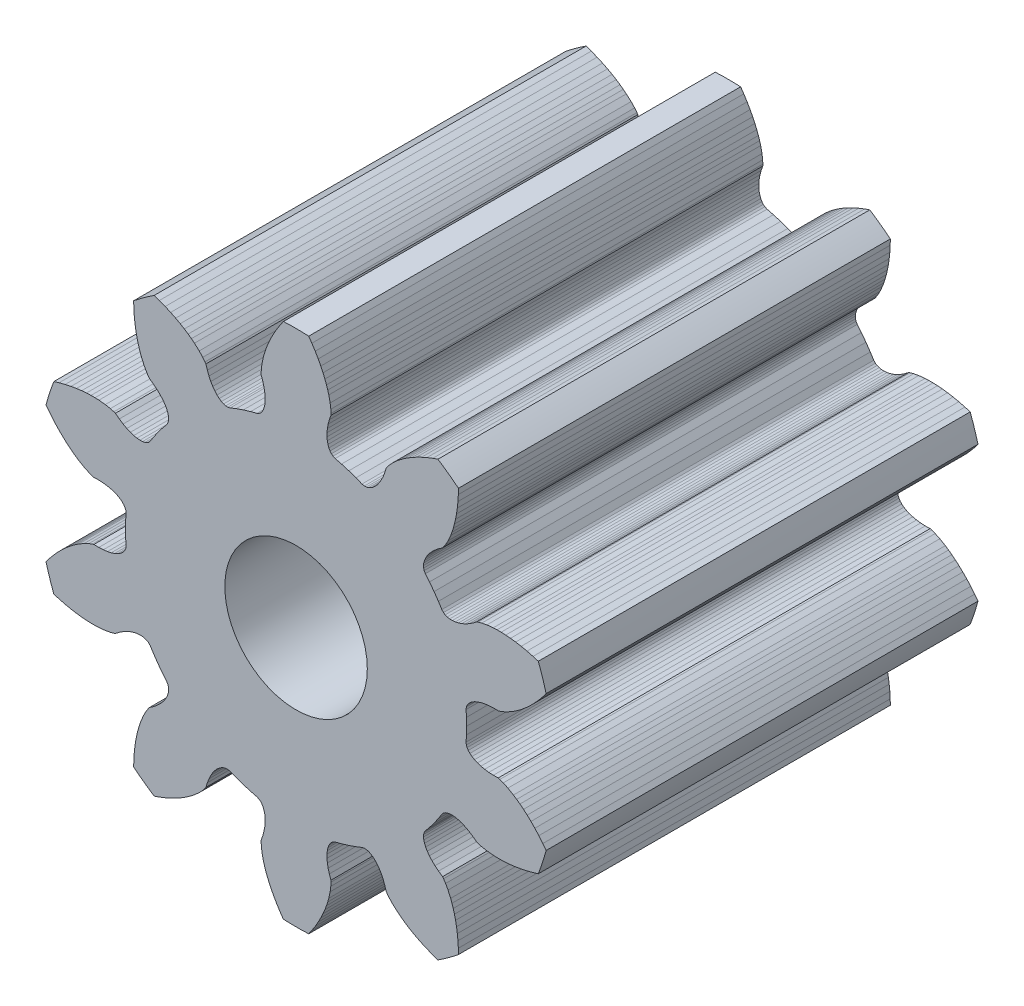
SolidWorks part; units mm, degrees
ref_plane "Front Plane" through (0, 0, 0) normal (0, 0, 1) x (1, 0, 0)
ref_plane "Top Plane" through (0, 0, 0) normal (0, 1, 0) x (1, 0, 0)
ref_plane "Right Plane" through (0, 0, 0) normal (1, 0, 0) x (0, 0, -1)
sketch "Sketch1" plane through (0, 0, 0) normal (0, 0, 1) x (1, 0, 0)
  line L0 (11.2428, -4.5485) -> (11.2517, -4.4039)
  line L1 (11.2517, -4.4039) -> (11.266, -4.2669)
  line L2 (11.266, -4.2669) -> (11.2847, -4.1393)
  line L3 (11.2847, -4.1393) -> (11.3071, -4.0209)
  line L4 (11.3071, -4.0209) -> (11.3325, -3.912)
  line L5 (11.3325, -3.912) -> (11.3608, -3.8103)
  line L6 (11.3608, -3.8103) -> (11.3897, -3.7211)
  line L7 (11.3897, -3.7211) -> (11.4208, -3.6371)
  line L8 (11.4208, -3.6371) -> (11.4807, -3.5016)
  line L9 (11.4807, -3.5016) -> (11.5377, -3.3971)
  line L10 (11.5377, -3.3971) -> (11.5845, -3.3262)
  line L11 (11.5845, -3.3262) -> (11.6076, -3.2964)
  line L12 (11.6076, -3.2964) -> (11.7007, -3.2317)
  line L13 (11.7007, -3.2317) -> (11.7827, -3.1653)
  line L14 (11.7827, -3.1653) -> (11.8533, -3.098)
  line L15 (11.8533, -3.098) -> (11.9128, -3.0308)
  line L16 (11.9128, -3.0308) -> (11.9612, -2.9643)
  line L17 (11.9612, -2.9643) -> (11.9989, -2.8995)
  line L18 (11.9989, -2.8995) -> (12.0259, -2.837)
  line L19 (12.0259, -2.837) -> (12.0426, -2.7776)
  line L20 (12.0426, -2.7776) -> (12.0493, -2.7222)
  line L21 (12.0493, -2.7222) -> (12.0463, -2.6714)
  line L22 (12.0463, -2.6714) -> (12.0342, -2.6259)
  line L23 (12.0342, -2.6259) -> (12.0067, -2.5776)
  line L24 (12.0067, -2.5776) -> (11.9109, -2.4617)
  line L25 (11.9109, -2.4617) -> (11.8044, -2.3217)
  line L26 (11.8044, -2.3217) -> (11.7041, -2.1772)
  line L27 (11.7041, -2.1772) -> (11.6236, -2.0503)
  line L28 (11.6236, -2.0503) -> (11.5861, -2.0092)
  line L29 (11.5861, -2.0092) -> (11.5466, -1.9836)
  line L30 (11.5466, -1.9836) -> (11.4992, -1.9651)
  line L31 (11.4992, -1.9651) -> (11.4444, -1.9543)
  line L32 (11.4444, -1.9543) -> (11.3828, -1.9518)
  line L33 (11.3828, -1.9518) -> (11.315, -1.9582)
  line L34 (11.315, -1.9582) -> (11.2417, -1.974)
  line L35 (11.2417, -1.974) -> (11.1635, -1.9995)
  line L36 (11.1635, -1.9995) -> (11.0812, -2.0353)
  line L37 (11.0812, -2.0353) -> (10.9954, -2.0817)
  line L38 (10.9954, -2.0817) -> (10.907, -2.1391)
  line L39 (10.907, -2.1391) -> (10.8166, -2.2077)
  line L40 (10.8166, -2.2077) -> (10.7811, -2.2204)
  line L41 (10.7811, -2.2204) -> (10.6992, -2.243)
  line L42 (10.6992, -2.243) -> (10.5823, -2.2649)
  line L43 (10.5823, -2.2649) -> (10.4348, -2.2801)
  line L44 (10.4348, -2.2801) -> (10.3453, -2.2837)
  line L45 (10.3453, -2.2837) -> (10.2516, -2.2836)
  line L46 (10.2516, -2.2836) -> (10.1461, -2.2791)
  line L47 (10.1461, -2.2791) -> (10.0348, -2.2696)
  line L48 (10.0348, -2.2696) -> (9.9151, -2.2543)
  line L49 (9.9151, -2.2543) -> (9.7881, -2.2327)
  line L50 (9.7881, -2.2327) -> (9.6533, -2.2039)
  line L51 (9.6533, -2.2039) -> (9.5131, -2.1677)
  line L52 (9.5131, -2.1677) -> (9.3912, -2.1311)
  line L53 (9.2098, -1.5726) -> (9.2868, -1.4714)
  line L54 (9.2868, -1.4714) -> (9.379, -1.3597)
  line L55 (9.379, -1.3597) -> (9.4711, -1.2572)
  line L56 (9.4711, -1.2572) -> (9.5612, -1.165)
  line L57 (9.5612, -1.165) -> (9.649, -1.0823)
  line L58 (9.649, -1.0823) -> (9.7335, -1.0092)
  line L59 (9.7335, -1.0092) -> (9.8162, -0.9435)
  line L60 (9.8162, -0.9435) -> (9.8919, -0.8883)
  line L61 (9.8919, -0.8883) -> (9.9665, -0.8387)
  line L62 (9.9665, -0.8387) -> (10.0947, -0.7642)
  line L63 (10.0947, -0.7642) -> (10.2021, -0.7133)
  line L64 (10.2021, -0.7133) -> (10.2817, -0.6834)
  line L65 (10.2817, -0.6834) -> (10.3179, -0.6728)
  line L66 (10.3179, -0.6728) -> (10.4313, -0.6752)
  line L67 (10.4313, -0.6752) -> (10.5366, -0.6696)
  line L68 (10.5366, -0.6696) -> (10.6333, -0.6568)
  line L69 (10.6333, -0.6568) -> (10.7209, -0.6373)
  line L70 (10.7209, -0.6373) -> (10.7992, -0.612)
  line L71 (10.7992, -0.612) -> (10.8678, -0.5817)
  line L72 (10.8678, -0.5817) -> (10.9263, -0.547)
  line L73 (10.9263, -0.547) -> (10.9747, -0.5088)
  line L74 (10.9747, -0.5088) -> (11.0127, -0.4679)
  line L75 (11.0127, -0.4679) -> (11.0402, -0.4251)
  line L76 (11.0402, -0.4251) -> (11.0571, -0.3811)
  line L77 (11.0571, -0.3811) -> (11.0633, -0.3259)
  line L78 (11.0633, -0.3259) -> (11.0539, -0.1759)
  line L79 (11.0539, -0.1759) -> (11.05, 0)
  line L80 (11.05, 0) -> (11.0539, 0.1759)
  line L81 (11.0539, 0.1759) -> (11.0633, 0.3259)
  line L82 (11.0633, 0.3259) -> (11.0571, 0.3812)
  line L83 (11.0571, 0.3812) -> (11.0402, 0.4251)
  line L84 (11.0402, 0.4251) -> (11.0127, 0.468)
  line L85 (11.0127, 0.468) -> (10.9747, 0.5089)
  line L86 (10.9747, 0.5089) -> (10.9263, 0.5471)
  line L87 (10.9263, 0.5471) -> (10.8678, 0.5817)
  line L88 (10.8678, 0.5817) -> (10.7992, 0.6121)
  line L89 (10.7992, 0.6121) -> (10.7209, 0.6374)
  line L90 (10.7209, 0.6374) -> (10.6333, 0.6568)
  line L91 (10.6333, 0.6568) -> (10.5366, 0.6697)
  line L92 (10.5366, 0.6697) -> (10.4313, 0.6753)
  line L93 (10.4313, 0.6753) -> (10.3179, 0.6729)
  line L94 (10.3179, 0.6729) -> (10.2817, 0.6834)
  line L95 (10.2817, 0.6834) -> (10.2021, 0.7133)
  line L96 (10.2021, 0.7133) -> (10.0947, 0.7643)
  line L97 (10.0947, 0.7643) -> (9.9665, 0.8387)
  line L98 (9.9665, 0.8387) -> (9.8919, 0.8884)
  line L99 (9.8919, 0.8884) -> (9.8162, 0.9436)
  line L100 (9.8162, 0.9436) -> (9.7335, 1.0093)
  line L101 (9.7335, 1.0093) -> (9.649, 1.0824)
  line L102 (9.649, 1.0824) -> (9.5612, 1.165)
  line L103 (9.5612, 1.165) -> (9.4711, 1.2572)
  line L104 (9.4711, 1.2572) -> (9.379, 1.3597)
  line L105 (9.379, 1.3597) -> (9.2868, 1.4714)
  line L106 (9.2868, 1.4714) -> (9.2098, 1.5727)
  line L107 (9.3912, 2.1311) -> (9.5131, 2.1677)
  line L108 (9.5131, 2.1677) -> (9.6533, 2.2039)
  line L109 (9.6533, 2.2039) -> (9.788, 2.2327)
  line L110 (9.788, 2.2327) -> (9.9151, 2.2544)
  line L111 (9.9151, 2.2544) -> (10.0347, 2.2696)
  line L112 (10.0347, 2.2696) -> (10.1461, 2.2791)
  line L113 (10.1461, 2.2791) -> (10.2516, 2.2836)
  line L114 (10.2516, 2.2836) -> (10.3453, 2.2837)
  line L115 (10.3453, 2.2837) -> (10.4348, 2.2801)
  line L116 (10.4348, 2.2801) -> (10.5823, 2.265)
  line L117 (10.5823, 2.265) -> (10.6992, 2.2431)
  line L118 (10.6992, 2.2431) -> (10.7811, 2.2205)
  line L119 (10.7811, 2.2205) -> (10.8166, 2.2078)
  line L120 (10.8166, 2.2078) -> (10.9069, 2.1391)
  line L121 (10.9069, 2.1391) -> (10.9954, 2.0818)
  line L122 (10.9954, 2.0818) -> (11.0812, 2.0353)
  line L123 (11.0812, 2.0353) -> (11.1635, 1.9995)
  line L124 (11.1635, 1.9995) -> (11.2417, 1.974)
  line L125 (11.2417, 1.974) -> (11.315, 1.9583)
  line L126 (11.315, 1.9583) -> (11.3828, 1.9519)
  line L127 (11.3828, 1.9519) -> (11.4444, 1.9543)
  line L128 (11.4444, 1.9543) -> (11.4991, 1.9651)
  line L129 (11.4991, 1.9651) -> (11.5465, 1.9836)
  line L130 (11.5465, 1.9836) -> (11.586, 2.0092)
  line L131 (11.586, 2.0092) -> (11.6235, 2.0503)
  line L132 (11.6235, 2.0503) -> (11.7041, 2.1772)
  line L133 (11.7041, 2.1772) -> (11.8043, 2.3218)
  line L134 (11.8043, 2.3218) -> (11.9109, 2.4618)
  line L135 (11.9109, 2.4618) -> (12.0067, 2.5776)
  line L136 (12.0067, 2.5776) -> (12.0341, 2.626)
  line L137 (12.0341, 2.626) -> (12.0463, 2.6715)
  line L138 (12.0463, 2.6715) -> (12.0492, 2.7223)
  line L139 (12.0492, 2.7223) -> (12.0426, 2.7777)
  line L140 (12.0426, 2.7777) -> (12.0259, 2.837)
  line L141 (12.0259, 2.837) -> (11.9988, 2.8995)
  line L142 (11.9988, 2.8995) -> (11.9612, 2.9643)
  line L143 (11.9612, 2.9643) -> (11.9128, 3.0308)
  line L144 (11.9128, 3.0308) -> (11.8533, 3.0981)
  line L145 (11.8533, 3.0981) -> (11.7826, 3.1653)
  line L146 (11.7826, 3.1653) -> (11.7007, 3.2317)
  line L147 (11.7007, 3.2317) -> (11.6075, 3.2964)
  line L148 (11.6075, 3.2964) -> (11.5845, 3.3262)
  line L149 (11.5845, 3.3262) -> (11.5377, 3.3972)
  line L150 (11.5377, 3.3972) -> (11.4807, 3.5016)
  line L151 (11.4807, 3.5016) -> (11.4208, 3.6372)
  line L152 (11.4208, 3.6372) -> (11.3896, 3.7212)
  line L153 (11.3896, 3.7212) -> (11.3608, 3.8103)
  line L154 (11.3608, 3.8103) -> (11.3325, 3.9121)
  line L155 (11.3325, 3.9121) -> (11.3071, 4.0209)
  line L156 (11.3071, 4.0209) -> (11.2846, 4.1394)
  line L157 (11.2846, 4.1394) -> (11.2659, 4.2669)
  line L158 (11.2659, 4.2669) -> (11.2517, 4.404)
  line L159 (11.2517, 4.404) -> (11.2428, 4.5485)
  line L160 (11.2428, 4.5485) -> (11.2399, 4.6757)
  line L161 (11.715, 5.0209) -> (11.8351, 4.9789)
  line L162 (11.8351, 4.9789) -> (11.9698, 4.9257)
  line L163 (11.9698, 4.9257) -> (12.0958, 4.8698)
  line L164 (12.0958, 4.8698) -> (12.2113, 4.8127)
  line L165 (12.2113, 4.8127) -> (12.3171, 4.7547)
  line L166 (12.3171, 4.7547) -> (12.4127, 4.6969)
  line L167 (12.4127, 4.6969) -> (12.5007, 4.6385)
  line L168 (12.5007, 4.6385) -> (12.5766, 4.5836)
  line L169 (12.5766, 4.5836) -> (12.6469, 4.528)
  line L170 (12.6469, 4.528) -> (12.7573, 4.4291)
  line L171 (12.7573, 4.4291) -> (12.839, 4.3427)
  line L172 (12.839, 4.3427) -> (12.892, 4.2762)
  line L173 (12.892, 4.2762) -> (12.9132, 4.2451)
  line L174 (12.9132, 4.2451) -> (12.946, 4.1364)
  line L175 (12.946, 4.1364) -> (12.9838, 4.038)
  line L176 (12.9838, 4.038) -> (13.0259, 3.9501)
  line L177 (13.0259, 3.9501) -> (13.0715, 3.8727)
  line L178 (13.0715, 3.8727) -> (13.1197, 3.8061)
  line L179 (13.1197, 3.8061) -> (13.1698, 3.7503)
  line L180 (13.1698, 3.7503) -> (13.2209, 3.7053)
  line L181 (13.2209, 3.7053) -> (13.2721, 3.671)
  line L182 (13.2721, 3.671) -> (13.3228, 3.6476)
  line L183 (13.3228, 3.6476) -> (13.372, 3.6347)
  line L184 (13.372, 3.6347) -> (13.419, 3.6322)
  line L185 (13.419, 3.6322) -> (13.4735, 3.6434)
  line L186 (13.4735, 3.6434) -> (13.6133, 3.6987)
  line L187 (13.6133, 3.6987) -> (13.7794, 3.7567)
  line L188 (13.7794, 3.7567) -> (13.9478, 3.8074)
  line L189 (13.9478, 3.8074) -> (14.0934, 3.8448)
  line L190 (14.0934, 3.8448) -> (14.1441, 3.8678)
  line L191 (14.1441, 3.8678) -> (14.1806, 3.8974)
  line L192 (14.1806, 3.8974) -> (14.2129, 3.9368)
  line L193 (14.2129, 3.9368) -> (14.2401, 3.9855)
  line L194 (14.2401, 3.9855) -> (14.2614, 4.0434)
  line L195 (14.2614, 4.0434) -> (14.2763, 4.1098)
  line L196 (14.2763, 4.1098) -> (14.284, 4.1844)
  line L197 (14.284, 4.1844) -> (14.2838, 4.2666)
  line L198 (14.2838, 4.2666) -> (14.2752, 4.356)
  line L199 (14.2752, 4.356) -> (14.2576, 4.4519)
  line L200 (14.2576, 4.4519) -> (14.2304, 4.5538)
  line L201 (14.2304, 4.5538) -> (14.193, 4.6609)
  line L202 (14.193, 4.6609) -> (14.1919, 4.6986)
  line L203 (14.1919, 4.6986) -> (14.1957, 4.7835)
  line L204 (14.1957, 4.7835) -> (14.211, 4.9014)
  line L205 (14.211, 4.9014) -> (14.2422, 5.0463)
  line L206 (14.2422, 5.0463) -> (14.2664, 5.1326)
  line L207 (14.2664, 5.1326) -> (14.2955, 5.2217)
  line L208 (14.2955, 5.2217) -> (14.3324, 5.3207)
  line L209 (14.3324, 5.3207) -> (14.3758, 5.4236)
  line L210 (14.3758, 5.4236) -> (14.4273, 5.5327)
  line L211 (14.4273, 5.5327) -> (14.4871, 5.6468)
  line L212 (14.4871, 5.6468) -> (14.5562, 5.7661)
  line L213 (14.5562, 5.7661) -> (14.6339, 5.8883)
  line L214 (14.6339, 5.8883) -> (14.7064, 5.9928)
  line L215 (15.2936, 5.9928) -> (15.3661, 5.8883)
  line L216 (15.3661, 5.8883) -> (15.4438, 5.7661)
  line L217 (15.4438, 5.7661) -> (15.5128, 5.6468)
  line L218 (15.5128, 5.6468) -> (15.5727, 5.5327)
  line L219 (15.5727, 5.5327) -> (15.6242, 5.4236)
  line L220 (15.6242, 5.4236) -> (15.6676, 5.3207)
  line L221 (15.6676, 5.3207) -> (15.7045, 5.2217)
  line L222 (15.7045, 5.2217) -> (15.7336, 5.1326)
  line L223 (15.7336, 5.1326) -> (15.7578, 5.0464)
  line L224 (15.7578, 5.0464) -> (15.7889, 4.9014)
  line L225 (15.7889, 4.9014) -> (15.8042, 4.7835)
  line L226 (15.8042, 4.7835) -> (15.8081, 4.6986)
  line L227 (15.8081, 4.6986) -> (15.8069, 4.6609)
  line L228 (15.8069, 4.6609) -> (15.7696, 4.5538)
  line L229 (15.7696, 4.5538) -> (15.7424, 4.4519)
  line L230 (15.7424, 4.4519) -> (15.7247, 4.356)
  line L231 (15.7247, 4.356) -> (15.7161, 4.2666)
  line L232 (15.7161, 4.2666) -> (15.716, 4.1844)
  line L233 (15.716, 4.1844) -> (15.7237, 4.1098)
  line L234 (15.7237, 4.1098) -> (15.7385, 4.0434)
  line L235 (15.7385, 4.0434) -> (15.7599, 3.9855)
  line L236 (15.7599, 3.9855) -> (15.7871, 3.9368)
  line L237 (15.7871, 3.9368) -> (15.8193, 3.8974)
  line L238 (15.8193, 3.8974) -> (15.8559, 3.8678)
  line L239 (15.8559, 3.8678) -> (15.9065, 3.8448)
  line L240 (15.9065, 3.8448) -> (16.0521, 3.8074)
  line L241 (16.0521, 3.8074) -> (16.2206, 3.7567)
  line L242 (16.2206, 3.7567) -> (16.3867, 3.6987)
  line L243 (16.3867, 3.6987) -> (16.5264, 3.6434)
  line L244 (16.5264, 3.6434) -> (16.5809, 3.6322)
  line L245 (16.5809, 3.6322) -> (16.6279, 3.6347)
  line L246 (16.6279, 3.6347) -> (16.6772, 3.6476)
  line L247 (16.6772, 3.6476) -> (16.7278, 3.6711)
  line L248 (16.7278, 3.6711) -> (16.7791, 3.7053)
  line L249 (16.7791, 3.7053) -> (16.8301, 3.7503)
  line L250 (16.8301, 3.7503) -> (16.8802, 3.8061)
  line L251 (16.8802, 3.8061) -> (16.9284, 3.8727)
  line L252 (16.9284, 3.8727) -> (16.974, 3.9501)
  line L253 (16.974, 3.9501) -> (17.0161, 4.038)
  line L254 (17.0161, 4.038) -> (17.054, 4.1365)
  line L255 (17.054, 4.1365) -> (17.0867, 4.2451)
  line L256 (17.0867, 4.2451) -> (17.108, 4.2762)
  line L257 (17.108, 4.2762) -> (17.161, 4.3427)
  line L258 (17.161, 4.3427) -> (17.2427, 4.4291)
  line L259 (17.2427, 4.4291) -> (17.3531, 4.528)
  line L260 (17.3531, 4.528) -> (17.4233, 4.5836)
  line L261 (17.4233, 4.5836) -> (17.4992, 4.6385)
  line L262 (17.4992, 4.6385) -> (17.5873, 4.6969)
  line L263 (17.5873, 4.6969) -> (17.6829, 4.7547)
  line L264 (17.6829, 4.7547) -> (17.7886, 4.8127)
  line L265 (17.7886, 4.8127) -> (17.9042, 4.8699)
  line L266 (17.9042, 4.8699) -> (18.0301, 4.9258)
  line L267 (18.0301, 4.9258) -> (18.1648, 4.9789)
  line L268 (18.1648, 4.9789) -> (18.2849, 5.0209)
  line L269 (18.76, 4.6758) -> (18.7572, 4.5486)
  line L270 (18.7572, 4.5486) -> (18.7483, 4.404)
  line L271 (18.7483, 4.404) -> (18.734, 4.2669)
  line L272 (18.734, 4.2669) -> (18.7153, 4.1394)
  line L273 (18.7153, 4.1394) -> (18.6928, 4.0209)
  line L274 (18.6928, 4.0209) -> (18.6675, 3.9121)
  line L275 (18.6675, 3.9121) -> (18.6392, 3.8103)
  line L276 (18.6392, 3.8103) -> (18.6103, 3.7212)
  line L277 (18.6103, 3.7212) -> (18.5792, 3.6372)
  line L278 (18.5792, 3.6372) -> (18.5192, 3.5016)
  line L279 (18.5192, 3.5016) -> (18.4623, 3.3972)
  line L280 (18.4623, 3.3972) -> (18.4155, 3.3263)
  line L281 (18.4155, 3.3263) -> (18.3924, 3.2965)
  line L282 (18.3924, 3.2965) -> (18.2992, 3.2317)
  line L283 (18.2992, 3.2317) -> (18.2173, 3.1653)
  line L284 (18.2173, 3.1653) -> (18.1467, 3.0981)
  line L285 (18.1467, 3.0981) -> (18.0872, 3.0308)
  line L286 (18.0872, 3.0308) -> (18.0387, 2.9644)
  line L287 (18.0387, 2.9644) -> (18.0011, 2.8995)
  line L288 (18.0011, 2.8995) -> (17.9741, 2.837)
  line L289 (17.9741, 2.837) -> (17.9574, 2.7777)
  line L290 (17.9574, 2.7777) -> (17.9507, 2.7223)
  line L291 (17.9507, 2.7223) -> (17.9537, 2.6715)
  line L292 (17.9537, 2.6715) -> (17.9658, 2.626)
  line L293 (17.9658, 2.626) -> (17.9933, 2.5777)
  line L294 (17.9933, 2.5777) -> (18.0891, 2.4618)
  line L295 (18.0891, 2.4618) -> (18.1956, 2.3218)
  line L296 (18.1956, 2.3218) -> (18.2959, 2.1772)
  line L297 (18.2959, 2.1772) -> (18.3764, 2.0503)
  line L298 (18.3764, 2.0503) -> (18.4139, 2.0093)
  line L299 (18.4139, 2.0093) -> (18.4534, 1.9836)
  line L300 (18.4534, 1.9836) -> (18.5008, 1.9651)
  line L301 (18.5008, 1.9651) -> (18.5556, 1.9544)
  line L302 (18.5556, 1.9544) -> (18.6172, 1.9519)
  line L303 (18.6172, 1.9519) -> (18.6849, 1.9583)
  line L304 (18.6849, 1.9583) -> (18.7583, 1.974)
  line L305 (18.7583, 1.974) -> (18.8364, 1.9996)
  line L306 (18.8364, 1.9996) -> (18.9188, 2.0354)
  line L307 (18.9188, 2.0354) -> (19.0046, 2.0818)
  line L308 (19.0046, 2.0818) -> (19.093, 2.1392)
  line L309 (19.093, 2.1392) -> (19.1834, 2.2078)
  line L310 (19.1834, 2.2078) -> (19.2188, 2.2205)
  line L311 (19.2188, 2.2205) -> (19.3008, 2.2431)
  line L312 (19.3008, 2.2431) -> (19.4177, 2.265)
  line L313 (19.4177, 2.265) -> (19.5651, 2.2801)
  line L314 (19.5651, 2.2801) -> (19.6547, 2.2838)
  line L315 (19.6547, 2.2838) -> (19.7484, 2.2837)
  line L316 (19.7484, 2.2837) -> (19.8539, 2.2791)
  line L317 (19.8539, 2.2791) -> (19.9652, 2.2696)
  line L318 (19.9652, 2.2696) -> (20.0848, 2.2544)
  line L319 (20.0848, 2.2544) -> (20.2119, 2.2328)
  line L320 (20.2119, 2.2328) -> (20.3467, 2.204)
  line L321 (20.3467, 2.204) -> (20.4869, 2.1678)
  line L322 (20.4869, 2.1678) -> (20.6088, 2.1312)
  line L323 (20.7902, 1.5727) -> (20.7132, 1.4714)
  line L324 (20.7132, 1.4714) -> (20.621, 1.3598)
  line L325 (20.621, 1.3598) -> (20.5289, 1.2572)
  line L326 (20.5289, 1.2572) -> (20.4388, 1.165)
  line L327 (20.4388, 1.165) -> (20.351, 1.0824)
  line L328 (20.351, 1.0824) -> (20.2665, 1.0093)
  line L329 (20.2665, 1.0093) -> (20.1838, 0.9436)
  line L330 (20.1838, 0.9436) -> (20.108, 0.8884)
  line L331 (20.108, 0.8884) -> (20.0335, 0.8388)
  line L332 (20.0335, 0.8388) -> (19.9053, 0.7643)
  line L333 (19.9053, 0.7643) -> (19.7979, 0.7133)
  line L334 (19.7979, 0.7133) -> (19.7183, 0.6834)
  line L335 (19.7183, 0.6834) -> (19.6821, 0.6729)
  line L336 (19.6821, 0.6729) -> (19.5687, 0.6753)
  line L337 (19.5687, 0.6753) -> (19.4634, 0.6697)
  line L338 (19.4634, 0.6697) -> (19.3667, 0.6568)
  line L339 (19.3667, 0.6568) -> (19.279, 0.6374)
  line L340 (19.279, 0.6374) -> (19.2008, 0.6121)
  line L341 (19.2008, 0.6121) -> (19.1322, 0.5818)
  line L342 (19.1322, 0.5818) -> (19.0736, 0.5471)
  line L343 (19.0736, 0.5471) -> (19.0253, 0.5089)
  line L344 (19.0253, 0.5089) -> (18.9873, 0.468)
  line L345 (18.9873, 0.468) -> (18.9598, 0.4252)
  line L346 (18.9598, 0.4252) -> (18.9429, 0.3812)
  line L347 (18.9429, 0.3812) -> (18.9367, 0.3259)
  line L348 (18.9367, 0.3259) -> (18.9461, 0.1759)
  line L349 (18.9461, 0.1759) -> (18.95, 0)
  line L350 (18.95, 0) -> (18.9461, -0.1758)
  line L351 (18.9461, -0.1758) -> (18.9367, -0.3259)
  line L352 (18.9367, -0.3259) -> (18.9429, -0.3811)
  line L353 (18.9429, -0.3811) -> (18.9598, -0.4251)
  line L354 (18.9598, -0.4251) -> (18.9873, -0.4679)
  line L355 (18.9873, -0.4679) -> (19.0253, -0.5088)
  line L356 (19.0253, -0.5088) -> (19.0736, -0.547)
  line L357 (19.0736, -0.547) -> (19.1322, -0.5817)
  line L358 (19.1322, -0.5817) -> (19.2008, -0.612)
  line L359 (19.2008, -0.612) -> (19.279, -0.6373)
  line L360 (19.279, -0.6373) -> (19.3667, -0.6567)
  line L361 (19.3667, -0.6567) -> (19.4634, -0.6696)
  line L362 (19.4634, -0.6696) -> (19.5687, -0.6752)
  line L363 (19.5687, -0.6752) -> (19.6821, -0.6728)
  line L364 (19.6821, -0.6728) -> (19.7183, -0.6834)
  line L365 (19.7183, -0.6834) -> (19.7979, -0.7132)
  line L366 (19.7979, -0.7132) -> (19.9053, -0.7642)
  line L367 (19.9053, -0.7642) -> (20.0335, -0.8387)
  line L368 (20.0335, -0.8387) -> (20.108, -0.8883)
  line L369 (20.108, -0.8883) -> (20.1838, -0.9435)
  line L370 (20.1838, -0.9435) -> (20.2665, -1.0092)
  line L371 (20.2665, -1.0092) -> (20.351, -1.0823)
  line L372 (20.351, -1.0823) -> (20.4388, -1.1649)
  line L373 (20.4388, -1.1649) -> (20.5289, -1.2571)
  line L374 (20.5289, -1.2571) -> (20.621, -1.3597)
  line L375 (20.621, -1.3597) -> (20.7132, -1.4714)
  line L376 (20.7132, -1.4714) -> (20.7902, -1.5726)
  line L377 (20.6088, -2.131) -> (20.4869, -2.1677)
  line L378 (20.4869, -2.1677) -> (20.3467, -2.2039)
  line L379 (20.3467, -2.2039) -> (20.2119, -2.2327)
  line L380 (20.2119, -2.2327) -> (20.0849, -2.2543)
  line L381 (20.0849, -2.2543) -> (19.9652, -2.2695)
  line L382 (19.9652, -2.2695) -> (19.8539, -2.279)
  line L383 (19.8539, -2.279) -> (19.7484, -2.2836)
  line L384 (19.7484, -2.2836) -> (19.6547, -2.2837)
  line L385 (19.6547, -2.2837) -> (19.5652, -2.28)
  line L386 (19.5652, -2.28) -> (19.4177, -2.2649)
  line L387 (19.4177, -2.2649) -> (19.3008, -2.243)
  line L388 (19.3008, -2.243) -> (19.2189, -2.2204)
  line L389 (19.2189, -2.2204) -> (19.1834, -2.2077)
  line L390 (19.1834, -2.2077) -> (19.093, -2.1391)
  line L391 (19.093, -2.1391) -> (19.0046, -2.0817)
  line L392 (19.0046, -2.0817) -> (18.9188, -2.0353)
  line L393 (18.9188, -2.0353) -> (18.8365, -1.9995)
  line L394 (18.8365, -1.9995) -> (18.7583, -1.9739)
  line L395 (18.7583, -1.9739) -> (18.685, -1.9582)
  line L396 (18.685, -1.9582) -> (18.6172, -1.9518)
  line L397 (18.6172, -1.9518) -> (18.5556, -1.9543)
  line L398 (18.5556, -1.9543) -> (18.5008, -1.965)
  line L399 (18.5008, -1.965) -> (18.4534, -1.9835)
  line L400 (18.4534, -1.9835) -> (18.4139, -2.0092)
  line L401 (18.4139, -2.0092) -> (18.3764, -2.0502)
  line L402 (18.3764, -2.0502) -> (18.2959, -2.1771)
  line L403 (18.2959, -2.1771) -> (18.1956, -2.3217)
  line L404 (18.1956, -2.3217) -> (18.0891, -2.4617)
  line L405 (18.0891, -2.4617) -> (17.9933, -2.5776)
  line L406 (17.9933, -2.5776) -> (17.9658, -2.6259)
  line L407 (17.9658, -2.6259) -> (17.9537, -2.6714)
  line L408 (17.9537, -2.6714) -> (17.9507, -2.7222)
  line L409 (17.9507, -2.7222) -> (17.9574, -2.7776)
  line L410 (17.9574, -2.7776) -> (17.9741, -2.8369)
  line L411 (17.9741, -2.8369) -> (18.0011, -2.8994)
  line L412 (18.0011, -2.8994) -> (18.0387, -2.9643)
  line L413 (18.0387, -2.9643) -> (18.0872, -3.0307)
  line L414 (18.0872, -3.0307) -> (18.1467, -3.098)
  line L415 (18.1467, -3.098) -> (18.2173, -3.1652)
  line L416 (18.2173, -3.1652) -> (18.2992, -3.2316)
  line L417 (18.2992, -3.2316) -> (18.3924, -3.2964)
  line L418 (18.3924, -3.2964) -> (18.4155, -3.3262)
  line L419 (18.4155, -3.3262) -> (18.4623, -3.3971)
  line L420 (18.4623, -3.3971) -> (18.5193, -3.5015)
  line L421 (18.5193, -3.5015) -> (18.5792, -3.6371)
  line L422 (18.5792, -3.6371) -> (18.6103, -3.7211)
  line L423 (18.6103, -3.7211) -> (18.6392, -3.8102)
  line L424 (18.6392, -3.8102) -> (18.6675, -3.912)
  line L425 (18.6675, -3.912) -> (18.6929, -4.0208)
  line L426 (18.6929, -4.0208) -> (18.7153, -4.1393)
  line L427 (18.7153, -4.1393) -> (18.734, -4.2668)
  line L428 (18.734, -4.2668) -> (18.7483, -4.4039)
  line L429 (18.7483, -4.4039) -> (18.7572, -4.5484)
  line L430 (18.7572, -4.5484) -> (18.76, -4.6757)
  line L431 (18.285, -5.0208) -> (18.1648, -4.9788)
  line L432 (18.1648, -4.9788) -> (18.0301, -4.9257)
  line L433 (18.0301, -4.9257) -> (17.9042, -4.8698)
  line L434 (17.9042, -4.8698) -> (17.7886, -4.8126)
  line L435 (17.7886, -4.8126) -> (17.6829, -4.7546)
  line L436 (17.6829, -4.7546) -> (17.5873, -4.6968)
  line L437 (17.5873, -4.6968) -> (17.4992, -4.6385)
  line L438 (17.4992, -4.6385) -> (17.4234, -4.5835)
  line L439 (17.4234, -4.5835) -> (17.3531, -4.5279)
  line L440 (17.3531, -4.5279) -> (17.2427, -4.429)
  line L441 (17.2427, -4.429) -> (17.161, -4.3426)
  line L442 (17.161, -4.3426) -> (17.108, -4.2761)
  line L443 (17.108, -4.2761) -> (17.0868, -4.245)
  line L444 (17.0868, -4.245) -> (17.054, -4.1364)
  line L445 (17.054, -4.1364) -> (17.0161, -4.038)
  line L446 (17.0161, -4.038) -> (16.974, -3.95)
  line L447 (16.974, -3.95) -> (16.9284, -3.8726)
  line L448 (16.9284, -3.8726) -> (16.8802, -3.806)
  line L449 (16.8802, -3.806) -> (16.8302, -3.7502)
  line L450 (16.8302, -3.7502) -> (16.7791, -3.7052)
  line L451 (16.7791, -3.7052) -> (16.7278, -3.671)
  line L452 (16.7278, -3.671) -> (16.6772, -3.6475)
  line L453 (16.6772, -3.6475) -> (16.6279, -3.6346)
  line L454 (16.6279, -3.6346) -> (16.5809, -3.6321)
  line L455 (16.5809, -3.6321) -> (16.5265, -3.6433)
  line L456 (16.5265, -3.6433) -> (16.3867, -3.6986)
  line L457 (16.3867, -3.6986) -> (16.2206, -3.7567)
  line L458 (16.2206, -3.7567) -> (16.0521, -3.8073)
  line L459 (16.0521, -3.8073) -> (15.9066, -3.8447)
  line L460 (15.9066, -3.8447) -> (15.8559, -3.8677)
  line L461 (15.8559, -3.8677) -> (15.8193, -3.8973)
  line L462 (15.8193, -3.8973) -> (15.7871, -3.9367)
  line L463 (15.7871, -3.9367) -> (15.7599, -3.9855)
  line L464 (15.7599, -3.9855) -> (15.7385, -4.0433)
  line L465 (15.7385, -4.0433) -> (15.7237, -4.1097)
  line L466 (15.7237, -4.1097) -> (15.716, -4.1843)
  line L467 (15.716, -4.1843) -> (15.7161, -4.2665)
  line L468 (15.7161, -4.2665) -> (15.7247, -4.3559)
  line L469 (15.7247, -4.3559) -> (15.7424, -4.4518)
  line L470 (15.7424, -4.4518) -> (15.7696, -4.5537)
  line L471 (15.7696, -4.5537) -> (15.8069, -4.6609)
  line L472 (15.8069, -4.6609) -> (15.8081, -4.6985)
  line L473 (15.8081, -4.6985) -> (15.8042, -4.7834)
  line L474 (15.8042, -4.7834) -> (15.789, -4.9014)
  line L475 (15.789, -4.9014) -> (15.7578, -5.0463)
  line L476 (15.7578, -5.0463) -> (15.7336, -5.1325)
  line L477 (15.7336, -5.1325) -> (15.7045, -5.2216)
  line L478 (15.7045, -5.2216) -> (15.6676, -5.3206)
  line L479 (15.6676, -5.3206) -> (15.6242, -5.4235)
  line L480 (15.6242, -5.4235) -> (15.5727, -5.5326)
  line L481 (15.5727, -5.5326) -> (15.5129, -5.6468)
  line L482 (15.5129, -5.6468) -> (15.4438, -5.766)
  line L483 (15.4438, -5.766) -> (15.3661, -5.8882)
  line L484 (15.3661, -5.8882) -> (15.2936, -5.9928)
  line L485 (14.7064, -5.9928) -> (14.6339, -5.8882)
  line L486 (14.6339, -5.8882) -> (14.5561, -5.766)
  line L487 (14.5561, -5.766) -> (14.4871, -5.6468)
  line L488 (14.4871, -5.6468) -> (14.4272, -5.5326)
  line L489 (14.4272, -5.5326) -> (14.3758, -5.4235)
  line L490 (14.3758, -5.4235) -> (14.3324, -5.3206)
  line L491 (14.3324, -5.3206) -> (14.2954, -5.2216)
  line L492 (14.2954, -5.2216) -> (14.2664, -5.1325)
  line L493 (14.2664, -5.1325) -> (14.2422, -5.0463)
  line L494 (14.2422, -5.0463) -> (14.211, -4.9014)
  line L495 (14.211, -4.9014) -> (14.1957, -4.7834)
  line L496 (14.1957, -4.7834) -> (14.1919, -4.6985)
  line L497 (14.1919, -4.6985) -> (14.193, -4.6608)
  line L498 (14.193, -4.6608) -> (14.2304, -4.5537)
  line L499 (14.2304, -4.5537) -> (14.2576, -4.4518)
  line L500 (14.2576, -4.4518) -> (14.2752, -4.3559)
  line L501 (14.2752, -4.3559) -> (14.2838, -4.2665)
  line L502 (14.2838, -4.2665) -> (14.284, -4.1843)
  line L503 (14.284, -4.1843) -> (14.2763, -4.1097)
  line L504 (14.2763, -4.1097) -> (14.2614, -4.0433)
  line L505 (14.2614, -4.0433) -> (14.24, -3.9855)
  line L506 (14.24, -3.9855) -> (14.2129, -3.9367)
  line L507 (14.2129, -3.9367) -> (14.1806, -3.8973)
  line L508 (14.1806, -3.8973) -> (14.144, -3.8677)
  line L509 (14.144, -3.8677) -> (14.0934, -3.8447)
  line L510 (14.0934, -3.8447) -> (13.9478, -3.8073)
  line L511 (13.9478, -3.8073) -> (13.7793, -3.7567)
  line L512 (13.7793, -3.7567) -> (13.6133, -3.6986)
  line L513 (13.6133, -3.6986) -> (13.4735, -3.6433)
  line L514 (13.4735, -3.6433) -> (13.419, -3.6321)
  line L515 (13.419, -3.6321) -> (13.372, -3.6346)
  line L516 (13.372, -3.6346) -> (13.3228, -3.6475)
  line L517 (13.3228, -3.6475) -> (13.2721, -3.671)
  line L518 (13.2721, -3.671) -> (13.2209, -3.7052)
  line L519 (13.2209, -3.7052) -> (13.1698, -3.7502)
  line L520 (13.1698, -3.7502) -> (13.1197, -3.806)
  line L521 (13.1197, -3.806) -> (13.0715, -3.8726)
  line L522 (13.0715, -3.8726) -> (13.0259, -3.95)
  line L523 (13.0259, -3.95) -> (12.9838, -4.038)
  line L524 (12.9838, -4.038) -> (12.946, -4.1364)
  line L525 (12.946, -4.1364) -> (12.9132, -4.245)
  line L526 (12.9132, -4.245) -> (12.892, -4.2761)
  line L527 (12.892, -4.2761) -> (12.839, -4.3426)
  line L528 (12.839, -4.3426) -> (12.7573, -4.429)
  line L529 (12.7573, -4.429) -> (12.6469, -4.5279)
  line L530 (12.6469, -4.5279) -> (12.5766, -4.5835)
  line L531 (12.5766, -4.5835) -> (12.5007, -4.6385)
  line L532 (12.5007, -4.6385) -> (12.4127, -4.6968)
  line L533 (12.4127, -4.6968) -> (12.317, -4.7546)
  line L534 (12.317, -4.7546) -> (12.2113, -4.8126)
  line L535 (12.2113, -4.8126) -> (12.0958, -4.8698)
  line L536 (12.0958, -4.8698) -> (11.9698, -4.9257)
  line L537 (11.9698, -4.9257) -> (11.8351, -4.9788)
  line L538 (11.8351, -4.9788) -> (11.715, -5.0208)
  line L539 (11.24, -4.6757) -> (11.2428, -4.5485)
  line L540 (11.2428, -4.5485) -> (11.2517, -4.4039)
  line L541 (11.2517, -4.4039) -> (11.266, -4.2669)
  line L542 (11.266, -4.2669) -> (11.2847, -4.1393)
  line L543 (11.2847, -4.1393) -> (11.3071, -4.0209)
  line L544 (11.3071, -4.0209) -> (11.3325, -3.912)
  line L545 (11.3325, -3.912) -> (11.3608, -3.8103)
  line L546 (11.3608, -3.8103) -> (11.3897, -3.7211)
  line L547 (11.3897, -3.7211) -> (11.4208, -3.6371)
  line L548 (11.4208, -3.6371) -> (11.4807, -3.5016)
  line L549 (11.4807, -3.5016) -> (11.5377, -3.3971)
  line L550 (11.5377, -3.3971) -> (11.5845, -3.3262)
  line L551 (11.5845, -3.3262) -> (11.6076, -3.2964)
  line L552 (11.6076, -3.2964) -> (11.7007, -3.2317)
  line L553 (11.7007, -3.2317) -> (11.7827, -3.1653)
  line L554 (11.7827, -3.1653) -> (11.8533, -3.098)
  line L555 (11.8533, -3.098) -> (11.9128, -3.0308)
  line L556 (11.9128, -3.0308) -> (11.9612, -2.9643)
  line L557 (11.9612, -2.9643) -> (11.9989, -2.8995)
  line L558 (11.9989, -2.8995) -> (12.0259, -2.837)
  line L559 (12.0259, -2.837) -> (12.0426, -2.7776)
  line L560 (12.0426, -2.7776) -> (12.0493, -2.7222)
  line L561 (12.0493, -2.7222) -> (12.0463, -2.6714)
  line L562 (12.0463, -2.6714) -> (12.0342, -2.6259)
  line L563 (12.0342, -2.6259) -> (12.0067, -2.5776)
  line L564 (12.0067, -2.5776) -> (11.9109, -2.4617)
  line L565 (11.9109, -2.4617) -> (11.8044, -2.3217)
  line L566 (11.8044, -2.3217) -> (11.7041, -2.1772)
  line L567 (11.7041, -2.1772) -> (11.6236, -2.0503)
  line L568 (11.6236, -2.0503) -> (11.5861, -2.0092)
  line L569 (11.5861, -2.0092) -> (11.5466, -1.9836)
  line L570 (11.5466, -1.9836) -> (11.4992, -1.9651)
  line L571 (11.4992, -1.9651) -> (11.4444, -1.9543)
  line L572 (11.4444, -1.9543) -> (11.3828, -1.9518)
  line L573 (11.3828, -1.9518) -> (11.315, -1.9582)
  line L574 (11.315, -1.9582) -> (11.2417, -1.974)
  line L575 (11.2417, -1.974) -> (11.1635, -1.9995)
  line L576 (11.1635, -1.9995) -> (11.0812, -2.0353)
  line L577 (11.0812, -2.0353) -> (10.9954, -2.0817)
  line L578 (10.9954, -2.0817) -> (10.907, -2.1391)
  line L579 (10.907, -2.1391) -> (10.8166, -2.2077)
  line L580 (10.8166, -2.2077) -> (10.7811, -2.2204)
  line L581 (10.7811, -2.2204) -> (10.6992, -2.243)
  line L582 (10.6992, -2.243) -> (10.5823, -2.2649)
  line L583 (10.5823, -2.2649) -> (10.4348, -2.2801)
  line L584 (10.4348, -2.2801) -> (10.3453, -2.2837)
  line L585 (10.3453, -2.2837) -> (10.2516, -2.2836)
  line L586 (10.2516, -2.2836) -> (10.1461, -2.2791)
  line L587 (10.1461, -2.2791) -> (10.0348, -2.2696)
  line L588 (10.0348, -2.2696) -> (9.9151, -2.2543)
  line L589 (9.9151, -2.2543) -> (9.7881, -2.2327)
  line L590 (9.7881, -2.2327) -> (9.6533, -2.2039)
  line L591 (9.6533, -2.2039) -> (9.5131, -2.1677)
  line L592 (9.5131, -2.1677) -> (9.3912, -2.1311)
  line L593 (9.2098, -1.5726) -> (9.2868, -1.4714)
  line L594 (9.2868, -1.4714) -> (9.379, -1.3597)
  line L595 (9.379, -1.3597) -> (9.4711, -1.2572)
  line L596 (9.4711, -1.2572) -> (9.5612, -1.165)
  line L597 (9.5612, -1.165) -> (9.649, -1.0823)
  line L598 (9.649, -1.0823) -> (9.7335, -1.0092)
  line L599 (9.7335, -1.0092) -> (9.8162, -0.9435)
  line L600 (9.8162, -0.9435) -> (9.8919, -0.8883)
  line L601 (9.8919, -0.8883) -> (9.9665, -0.8387)
  line L602 (9.9665, -0.8387) -> (10.0947, -0.7642)
  line L603 (10.0947, -0.7642) -> (10.2021, -0.7133)
  line L604 (10.2021, -0.7133) -> (10.2817, -0.6834)
  line L605 (10.2817, -0.6834) -> (10.3179, -0.6728)
  line L606 (10.3179, -0.6728) -> (10.4313, -0.6752)
  line L607 (10.4313, -0.6752) -> (10.5366, -0.6696)
  line L608 (10.5366, -0.6696) -> (10.6333, -0.6568)
  line L609 (10.6333, -0.6568) -> (10.7209, -0.6373)
  line L610 (10.7209, -0.6373) -> (10.7992, -0.612)
  line L611 (10.7992, -0.612) -> (10.8678, -0.5817)
  line L612 (10.8678, -0.5817) -> (10.9263, -0.547)
  line L613 (10.9263, -0.547) -> (10.9747, -0.5088)
  line L614 (10.9747, -0.5088) -> (11.0127, -0.4679)
  line L615 (11.0127, -0.4679) -> (11.0402, -0.4251)
  line L616 (11.0402, -0.4251) -> (11.0571, -0.3811)
  line L617 (11.0571, -0.3811) -> (11.0633, -0.3259)
  line L618 (11.0633, -0.3259) -> (11.0539, -0.1759)
  line L619 (11.0539, -0.1759) -> (11.05, 0)
  line L620 (11.05, 0) -> (11.0539, 0.1759)
  line L621 (11.0539, 0.1759) -> (11.0633, 0.3259)
  line L622 (11.0633, 0.3259) -> (11.0571, 0.3812)
  line L623 (11.0571, 0.3812) -> (11.0402, 0.4251)
  line L624 (11.0402, 0.4251) -> (11.0127, 0.468)
  line L625 (11.0127, 0.468) -> (10.9747, 0.5089)
  line L626 (10.9747, 0.5089) -> (10.9263, 0.5471)
  line L627 (10.9263, 0.5471) -> (10.8678, 0.5817)
  line L628 (10.8678, 0.5817) -> (10.7992, 0.6121)
  line L629 (10.7992, 0.6121) -> (10.7209, 0.6374)
  line L630 (10.7209, 0.6374) -> (10.6333, 0.6568)
  line L631 (10.6333, 0.6568) -> (10.5366, 0.6697)
  line L632 (10.5366, 0.6697) -> (10.4313, 0.6753)
  line L633 (10.4313, 0.6753) -> (10.3179, 0.6729)
  line L634 (10.3179, 0.6729) -> (10.2817, 0.6834)
  line L635 (10.2817, 0.6834) -> (10.2021, 0.7133)
  line L636 (10.2021, 0.7133) -> (10.0947, 0.7643)
  line L637 (10.0947, 0.7643) -> (9.9665, 0.8387)
  line L638 (9.9665, 0.8387) -> (9.8919, 0.8884)
  line L639 (9.8919, 0.8884) -> (9.8162, 0.9436)
  line L640 (9.8162, 0.9436) -> (9.7335, 1.0093)
  line L641 (9.7335, 1.0093) -> (9.649, 1.0824)
  line L642 (9.649, 1.0824) -> (9.5612, 1.165)
  line L643 (9.5612, 1.165) -> (9.4711, 1.2572)
  line L644 (9.4711, 1.2572) -> (9.379, 1.3597)
  line L645 (9.379, 1.3597) -> (9.2868, 1.4714)
  line L646 (9.2868, 1.4714) -> (9.2098, 1.5727)
  line L647 (9.3912, 2.1311) -> (9.5131, 2.1677)
  line L648 (9.5131, 2.1677) -> (9.6533, 2.2039)
  line L649 (9.6533, 2.2039) -> (9.788, 2.2327)
  line L650 (9.788, 2.2327) -> (9.9151, 2.2544)
  line L651 (9.9151, 2.2544) -> (10.0347, 2.2696)
  line L652 (10.0347, 2.2696) -> (10.1461, 2.2791)
  line L653 (10.1461, 2.2791) -> (10.2516, 2.2836)
  line L654 (10.2516, 2.2836) -> (10.3453, 2.2837)
  line L655 (10.3453, 2.2837) -> (10.4348, 2.2801)
  line L656 (10.4348, 2.2801) -> (10.5823, 2.265)
  line L657 (10.5823, 2.265) -> (10.6992, 2.2431)
  line L658 (10.6992, 2.2431) -> (10.7811, 2.2205)
  line L659 (10.7811, 2.2205) -> (10.8166, 2.2078)
  line L660 (10.8166, 2.2078) -> (10.9069, 2.1391)
  line L661 (10.9069, 2.1391) -> (10.9954, 2.0818)
  line L662 (10.9954, 2.0818) -> (11.0812, 2.0353)
  line L663 (11.0812, 2.0353) -> (11.1635, 1.9995)
  line L664 (11.1635, 1.9995) -> (11.2417, 1.974)
  line L665 (11.2417, 1.974) -> (11.315, 1.9583)
  line L666 (11.315, 1.9583) -> (11.3828, 1.9519)
  line L667 (11.3828, 1.9519) -> (11.4444, 1.9543)
  line L668 (11.4444, 1.9543) -> (11.4991, 1.9651)
  line L669 (11.4991, 1.9651) -> (11.5465, 1.9836)
  line L670 (11.5465, 1.9836) -> (11.586, 2.0092)
  line L671 (11.586, 2.0092) -> (11.6235, 2.0503)
  line L672 (11.6235, 2.0503) -> (11.7041, 2.1772)
  line L673 (11.7041, 2.1772) -> (11.8043, 2.3218)
  line L674 (11.8043, 2.3218) -> (11.9109, 2.4618)
  line L675 (11.9109, 2.4618) -> (12.0067, 2.5776)
  line L676 (12.0067, 2.5776) -> (12.0341, 2.626)
  line L677 (12.0341, 2.626) -> (12.0463, 2.6715)
  line L678 (12.0463, 2.6715) -> (12.0492, 2.7223)
  line L679 (12.0492, 2.7223) -> (12.0426, 2.7777)
  line L680 (12.0426, 2.7777) -> (12.0259, 2.837)
  line L681 (12.0259, 2.837) -> (11.9988, 2.8995)
  line L682 (11.9988, 2.8995) -> (11.9612, 2.9643)
  line L683 (11.9612, 2.9643) -> (11.9128, 3.0308)
  line L684 (11.9128, 3.0308) -> (11.8533, 3.0981)
  line L685 (11.8533, 3.0981) -> (11.7826, 3.1653)
  line L686 (11.7826, 3.1653) -> (11.7007, 3.2317)
  line L687 (11.7007, 3.2317) -> (11.6075, 3.2964)
  line L688 (11.6075, 3.2964) -> (11.5845, 3.3262)
  line L689 (11.5845, 3.3262) -> (11.5377, 3.3972)
  line L690 (11.5377, 3.3972) -> (11.4807, 3.5016)
  line L691 (11.4807, 3.5016) -> (11.4208, 3.6372)
  line L692 (11.4208, 3.6372) -> (11.3896, 3.7212)
  line L693 (11.3896, 3.7212) -> (11.3608, 3.8103)
  line L694 (11.3608, 3.8103) -> (11.3325, 3.9121)
  line L695 (11.3325, 3.9121) -> (11.3071, 4.0209)
  line L696 (11.3071, 4.0209) -> (11.2846, 4.1394)
  line L697 (11.2846, 4.1394) -> (11.2659, 4.2669)
  line L698 (11.2659, 4.2669) -> (11.2517, 4.404)
  line L699 (11.2517, 4.404) -> (11.2428, 4.5485)
  line L700 (11.2428, 4.5485) -> (11.2399, 4.6757)
  line L701 (11.715, 5.0209) -> (11.8351, 4.9789)
  line L702 (11.8351, 4.9789) -> (11.9698, 4.9257)
  line L703 (11.9698, 4.9257) -> (12.0958, 4.8698)
  line L704 (12.0958, 4.8698) -> (12.2113, 4.8127)
  line L705 (12.2113, 4.8127) -> (12.3171, 4.7547)
  line L706 (12.3171, 4.7547) -> (12.4127, 4.6969)
  line L707 (12.4127, 4.6969) -> (12.5007, 4.6385)
  line L708 (12.5007, 4.6385) -> (12.5766, 4.5836)
  line L709 (12.5766, 4.5836) -> (12.6469, 4.528)
  line L710 (12.6469, 4.528) -> (12.7573, 4.4291)
  line L711 (12.7573, 4.4291) -> (12.839, 4.3427)
  line L712 (12.839, 4.3427) -> (12.892, 4.2762)
  line L713 (12.892, 4.2762) -> (12.9132, 4.2451)
  line L714 (12.9132, 4.2451) -> (12.946, 4.1364)
  line L715 (12.946, 4.1364) -> (12.9838, 4.038)
  line L716 (12.9838, 4.038) -> (13.0259, 3.9501)
  line L717 (13.0259, 3.9501) -> (13.0715, 3.8727)
  line L718 (13.0715, 3.8727) -> (13.1197, 3.8061)
  line L719 (13.1197, 3.8061) -> (13.1698, 3.7503)
  line L720 (13.1698, 3.7503) -> (13.2209, 3.7053)
  line L721 (13.2209, 3.7053) -> (13.2721, 3.671)
  line L722 (13.2721, 3.671) -> (13.3228, 3.6476)
  line L723 (13.3228, 3.6476) -> (13.372, 3.6347)
  line L724 (13.372, 3.6347) -> (13.419, 3.6322)
  line L725 (13.419, 3.6322) -> (13.4735, 3.6434)
  line L726 (13.4735, 3.6434) -> (13.6133, 3.6987)
  line L727 (13.6133, 3.6987) -> (13.7794, 3.7567)
  line L728 (13.7794, 3.7567) -> (13.9478, 3.8074)
  line L729 (13.9478, 3.8074) -> (14.0934, 3.8448)
  line L730 (14.0934, 3.8448) -> (14.1441, 3.8678)
  line L731 (14.1441, 3.8678) -> (14.1806, 3.8974)
  line L732 (14.1806, 3.8974) -> (14.2129, 3.9368)
  line L733 (14.2129, 3.9368) -> (14.2401, 3.9855)
  line L734 (14.2401, 3.9855) -> (14.2614, 4.0434)
  line L735 (14.2614, 4.0434) -> (14.2763, 4.1098)
  line L736 (14.2763, 4.1098) -> (14.284, 4.1844)
  line L737 (14.284, 4.1844) -> (14.2838, 4.2666)
  line L738 (14.2838, 4.2666) -> (14.2752, 4.356)
  line L739 (14.2752, 4.356) -> (14.2576, 4.4519)
  line L740 (14.2576, 4.4519) -> (14.2304, 4.5538)
  line L741 (14.2304, 4.5538) -> (14.193, 4.6609)
  line L742 (14.193, 4.6609) -> (14.1919, 4.6986)
  line L743 (14.1919, 4.6986) -> (14.1957, 4.7835)
  line L744 (14.1957, 4.7835) -> (14.211, 4.9014)
  line L745 (14.211, 4.9014) -> (14.2422, 5.0463)
  line L746 (14.2422, 5.0463) -> (14.2664, 5.1326)
  line L747 (14.2664, 5.1326) -> (14.2955, 5.2217)
  line L748 (14.2955, 5.2217) -> (14.3324, 5.3207)
  line L749 (14.3324, 5.3207) -> (14.3758, 5.4236)
  line L750 (14.3758, 5.4236) -> (14.4273, 5.5327)
  line L751 (14.4273, 5.5327) -> (14.4871, 5.6468)
  line L752 (14.4871, 5.6468) -> (14.5562, 5.7661)
  line L753 (14.5562, 5.7661) -> (14.6339, 5.8883)
  line L754 (14.6339, 5.8883) -> (14.7064, 5.9928)
  line L755 (15.2936, 5.9928) -> (15.3661, 5.8883)
  line L756 (15.3661, 5.8883) -> (15.4438, 5.7661)
  line L757 (15.4438, 5.7661) -> (15.5128, 5.6468)
  line L758 (15.5128, 5.6468) -> (15.5727, 5.5327)
  line L759 (15.5727, 5.5327) -> (15.6242, 5.4236)
  line L760 (15.6242, 5.4236) -> (15.6676, 5.3207)
  line L761 (15.6676, 5.3207) -> (15.7045, 5.2217)
  line L762 (15.7045, 5.2217) -> (15.7336, 5.1326)
  line L763 (15.7336, 5.1326) -> (15.7578, 5.0464)
  line L764 (15.7578, 5.0464) -> (15.7889, 4.9014)
  line L765 (15.7889, 4.9014) -> (15.8042, 4.7835)
  line L766 (15.8042, 4.7835) -> (15.8081, 4.6986)
  line L767 (15.8081, 4.6986) -> (15.8069, 4.6609)
  line L768 (15.8069, 4.6609) -> (15.7696, 4.5538)
  line L769 (15.7696, 4.5538) -> (15.7424, 4.4519)
  line L770 (15.7424, 4.4519) -> (15.7247, 4.356)
  line L771 (15.7247, 4.356) -> (15.7161, 4.2666)
  line L772 (15.7161, 4.2666) -> (15.716, 4.1844)
  line L773 (15.716, 4.1844) -> (15.7237, 4.1098)
  line L774 (15.7237, 4.1098) -> (15.7385, 4.0434)
  line L775 (15.7385, 4.0434) -> (15.7599, 3.9855)
  line L776 (15.7599, 3.9855) -> (15.7871, 3.9368)
  line L777 (15.7871, 3.9368) -> (15.8193, 3.8974)
  line L778 (15.8193, 3.8974) -> (15.8559, 3.8678)
  line L779 (15.8559, 3.8678) -> (15.9065, 3.8448)
  line L780 (15.9065, 3.8448) -> (16.0521, 3.8074)
  line L781 (16.0521, 3.8074) -> (16.2206, 3.7567)
  line L782 (16.2206, 3.7567) -> (16.3867, 3.6987)
  line L783 (16.3867, 3.6987) -> (16.5264, 3.6434)
  line L784 (16.5264, 3.6434) -> (16.5809, 3.6322)
  line L785 (16.5809, 3.6322) -> (16.6279, 3.6347)
  line L786 (16.6279, 3.6347) -> (16.6772, 3.6476)
  line L787 (16.6772, 3.6476) -> (16.7278, 3.6711)
  line L788 (16.7278, 3.6711) -> (16.7791, 3.7053)
  line L789 (16.7791, 3.7053) -> (16.8301, 3.7503)
  line L790 (16.8301, 3.7503) -> (16.8802, 3.8061)
  line L791 (16.8802, 3.8061) -> (16.9284, 3.8727)
  line L792 (16.9284, 3.8727) -> (16.974, 3.9501)
  line L793 (16.974, 3.9501) -> (17.0161, 4.038)
  line L794 (17.0161, 4.038) -> (17.054, 4.1365)
  line L795 (17.054, 4.1365) -> (17.0867, 4.2451)
  line L796 (17.0867, 4.2451) -> (17.108, 4.2762)
  line L797 (17.108, 4.2762) -> (17.161, 4.3427)
  line L798 (17.161, 4.3427) -> (17.2427, 4.4291)
  line L799 (17.2427, 4.4291) -> (17.3531, 4.528)
  line L800 (17.3531, 4.528) -> (17.4233, 4.5836)
  line L801 (17.4233, 4.5836) -> (17.4992, 4.6385)
  line L802 (17.4992, 4.6385) -> (17.5873, 4.6969)
  line L803 (17.5873, 4.6969) -> (17.6829, 4.7547)
  line L804 (17.6829, 4.7547) -> (17.7886, 4.8127)
  line L805 (17.7886, 4.8127) -> (17.9042, 4.8699)
  line L806 (17.9042, 4.8699) -> (18.0301, 4.9258)
  line L807 (18.0301, 4.9258) -> (18.1648, 4.9789)
  line L808 (18.1648, 4.9789) -> (18.2849, 5.0209)
  line L809 (18.76, 4.6758) -> (18.7572, 4.5486)
  line L810 (18.7572, 4.5486) -> (18.7483, 4.404)
  line L811 (18.7483, 4.404) -> (18.734, 4.2669)
  line L812 (18.734, 4.2669) -> (18.7153, 4.1394)
  line L813 (18.7153, 4.1394) -> (18.6928, 4.0209)
  line L814 (18.6928, 4.0209) -> (18.6675, 3.9121)
  line L815 (18.6675, 3.9121) -> (18.6392, 3.8103)
  line L816 (18.6392, 3.8103) -> (18.6103, 3.7212)
  line L817 (18.6103, 3.7212) -> (18.5792, 3.6372)
  line L818 (18.5792, 3.6372) -> (18.5192, 3.5016)
  line L819 (18.5192, 3.5016) -> (18.4623, 3.3972)
  line L820 (18.4623, 3.3972) -> (18.4155, 3.3263)
  line L821 (18.4155, 3.3263) -> (18.3924, 3.2965)
  line L822 (18.3924, 3.2965) -> (18.2992, 3.2317)
  line L823 (18.2992, 3.2317) -> (18.2173, 3.1653)
  line L824 (18.2173, 3.1653) -> (18.1467, 3.0981)
  line L825 (18.1467, 3.0981) -> (18.0872, 3.0308)
  line L826 (18.0872, 3.0308) -> (18.0387, 2.9644)
  line L827 (18.0387, 2.9644) -> (18.0011, 2.8995)
  line L828 (18.0011, 2.8995) -> (17.9741, 2.837)
  line L829 (17.9741, 2.837) -> (17.9574, 2.7777)
  line L830 (17.9574, 2.7777) -> (17.9507, 2.7223)
  line L831 (17.9507, 2.7223) -> (17.9537, 2.6715)
  line L832 (17.9537, 2.6715) -> (17.9658, 2.626)
  line L833 (17.9658, 2.626) -> (17.9933, 2.5777)
  line L834 (17.9933, 2.5777) -> (18.0891, 2.4618)
  line L835 (18.0891, 2.4618) -> (18.1956, 2.3218)
  line L836 (18.1956, 2.3218) -> (18.2959, 2.1772)
  line L837 (18.2959, 2.1772) -> (18.3764, 2.0503)
  line L838 (18.3764, 2.0503) -> (18.4139, 2.0093)
  line L839 (18.4139, 2.0093) -> (18.4534, 1.9836)
  line L840 (18.4534, 1.9836) -> (18.5008, 1.9651)
  line L841 (18.5008, 1.9651) -> (18.5556, 1.9544)
  line L842 (18.5556, 1.9544) -> (18.6172, 1.9519)
  line L843 (18.6172, 1.9519) -> (18.6849, 1.9583)
  line L844 (18.6849, 1.9583) -> (18.7583, 1.974)
  line L845 (18.7583, 1.974) -> (18.8364, 1.9996)
  line L846 (18.8364, 1.9996) -> (18.9188, 2.0354)
  line L847 (18.9188, 2.0354) -> (19.0046, 2.0818)
  line L848 (19.0046, 2.0818) -> (19.093, 2.1392)
  line L849 (19.093, 2.1392) -> (19.1834, 2.2078)
  line L850 (19.1834, 2.2078) -> (19.2188, 2.2205)
  line L851 (19.2188, 2.2205) -> (19.3008, 2.2431)
  line L852 (19.3008, 2.2431) -> (19.4177, 2.265)
  line L853 (19.4177, 2.265) -> (19.5651, 2.2801)
  line L854 (19.5651, 2.2801) -> (19.6547, 2.2838)
  line L855 (19.6547, 2.2838) -> (19.7484, 2.2837)
  line L856 (19.7484, 2.2837) -> (19.8539, 2.2791)
  line L857 (19.8539, 2.2791) -> (19.9652, 2.2696)
  line L858 (19.9652, 2.2696) -> (20.0848, 2.2544)
  line L859 (20.0848, 2.2544) -> (20.2119, 2.2328)
  line L860 (20.2119, 2.2328) -> (20.3467, 2.204)
  line L861 (20.3467, 2.204) -> (20.4869, 2.1678)
  line L862 (20.4869, 2.1678) -> (20.6088, 2.1312)
  line L863 (20.7902, 1.5727) -> (20.7132, 1.4714)
  line L864 (20.7132, 1.4714) -> (20.621, 1.3598)
  line L865 (20.621, 1.3598) -> (20.5289, 1.2572)
  line L866 (20.5289, 1.2572) -> (20.4388, 1.165)
  line L867 (20.4388, 1.165) -> (20.351, 1.0824)
  line L868 (20.351, 1.0824) -> (20.2665, 1.0093)
  line L869 (20.2665, 1.0093) -> (20.1838, 0.9436)
  line L870 (20.1838, 0.9436) -> (20.108, 0.8884)
  line L871 (20.108, 0.8884) -> (20.0335, 0.8388)
  line L872 (20.0335, 0.8388) -> (19.9053, 0.7643)
  line L873 (19.9053, 0.7643) -> (19.7979, 0.7133)
  line L874 (19.7979, 0.7133) -> (19.7183, 0.6834)
  line L875 (19.7183, 0.6834) -> (19.6821, 0.6729)
  line L876 (19.6821, 0.6729) -> (19.5687, 0.6753)
  line L877 (19.5687, 0.6753) -> (19.4634, 0.6697)
  line L878 (19.4634, 0.6697) -> (19.3667, 0.6568)
  line L879 (19.3667, 0.6568) -> (19.279, 0.6374)
  line L880 (19.279, 0.6374) -> (19.2008, 0.6121)
  line L881 (19.2008, 0.6121) -> (19.1322, 0.5818)
  line L882 (19.1322, 0.5818) -> (19.0736, 0.5471)
  line L883 (19.0736, 0.5471) -> (19.0253, 0.5089)
  line L884 (19.0253, 0.5089) -> (18.9873, 0.468)
  line L885 (18.9873, 0.468) -> (18.9598, 0.4252)
  line L886 (18.9598, 0.4252) -> (18.9429, 0.3812)
  line L887 (18.9429, 0.3812) -> (18.9367, 0.3259)
  line L888 (18.9367, 0.3259) -> (18.9461, 0.1759)
  line L889 (18.9461, 0.1759) -> (18.95, 0)
  line L890 (18.95, 0) -> (18.9461, -0.1758)
  line L891 (18.9461, -0.1758) -> (18.9367, -0.3259)
  line L892 (18.9367, -0.3259) -> (18.9429, -0.3811)
  line L893 (18.9429, -0.3811) -> (18.9598, -0.4251)
  line L894 (18.9598, -0.4251) -> (18.9873, -0.4679)
  line L895 (18.9873, -0.4679) -> (19.0253, -0.5088)
  line L896 (19.0253, -0.5088) -> (19.0736, -0.547)
  line L897 (19.0736, -0.547) -> (19.1322, -0.5817)
  line L898 (19.1322, -0.5817) -> (19.2008, -0.612)
  line L899 (19.2008, -0.612) -> (19.279, -0.6373)
  line L900 (19.279, -0.6373) -> (19.3667, -0.6567)
  line L901 (19.3667, -0.6567) -> (19.4634, -0.6696)
  line L902 (19.4634, -0.6696) -> (19.5687, -0.6752)
  line L903 (19.5687, -0.6752) -> (19.6821, -0.6728)
  line L904 (19.6821, -0.6728) -> (19.7183, -0.6834)
  line L905 (19.7183, -0.6834) -> (19.7979, -0.7132)
  line L906 (19.7979, -0.7132) -> (19.9053, -0.7642)
  line L907 (19.9053, -0.7642) -> (20.0335, -0.8387)
  line L908 (20.0335, -0.8387) -> (20.108, -0.8883)
  line L909 (20.108, -0.8883) -> (20.1838, -0.9435)
  line L910 (20.1838, -0.9435) -> (20.2665, -1.0092)
  line L911 (20.2665, -1.0092) -> (20.351, -1.0823)
  line L912 (20.351, -1.0823) -> (20.4388, -1.1649)
  line L913 (20.4388, -1.1649) -> (20.5289, -1.2571)
  line L914 (20.5289, -1.2571) -> (20.621, -1.3597)
  line L915 (20.621, -1.3597) -> (20.7132, -1.4714)
  line L916 (20.7132, -1.4714) -> (20.7902, -1.5726)
  line L917 (20.6088, -2.131) -> (20.4869, -2.1677)
  line L918 (20.4869, -2.1677) -> (20.3467, -2.2039)
  line L919 (20.3467, -2.2039) -> (20.2119, -2.2327)
  line L920 (20.2119, -2.2327) -> (20.0849, -2.2543)
  line L921 (20.0849, -2.2543) -> (19.9652, -2.2695)
  line L922 (19.9652, -2.2695) -> (19.8539, -2.279)
  line L923 (19.8539, -2.279) -> (19.7484, -2.2836)
  line L924 (19.7484, -2.2836) -> (19.6547, -2.2837)
  line L925 (19.6547, -2.2837) -> (19.5652, -2.28)
  line L926 (19.5652, -2.28) -> (19.4177, -2.2649)
  line L927 (19.4177, -2.2649) -> (19.3008, -2.243)
  line L928 (19.3008, -2.243) -> (19.2189, -2.2204)
  line L929 (19.2189, -2.2204) -> (19.1834, -2.2077)
  line L930 (19.1834, -2.2077) -> (19.093, -2.1391)
  line L931 (19.093, -2.1391) -> (19.0046, -2.0817)
  line L932 (19.0046, -2.0817) -> (18.9188, -2.0353)
  line L933 (18.9188, -2.0353) -> (18.8365, -1.9995)
  line L934 (18.8365, -1.9995) -> (18.7583, -1.9739)
  line L935 (18.7583, -1.9739) -> (18.685, -1.9582)
  line L936 (18.685, -1.9582) -> (18.6172, -1.9518)
  line L937 (18.6172, -1.9518) -> (18.5556, -1.9543)
  line L938 (18.5556, -1.9543) -> (18.5008, -1.965)
  line L939 (18.5008, -1.965) -> (18.4534, -1.9835)
  line L940 (18.4534, -1.9835) -> (18.4139, -2.0092)
  line L941 (18.4139, -2.0092) -> (18.3764, -2.0502)
  line L942 (18.3764, -2.0502) -> (18.2959, -2.1771)
  line L943 (18.2959, -2.1771) -> (18.1956, -2.3217)
  line L944 (18.1956, -2.3217) -> (18.0891, -2.4617)
  line L945 (18.0891, -2.4617) -> (17.9933, -2.5776)
  line L946 (17.9933, -2.5776) -> (17.9658, -2.6259)
  line L947 (17.9658, -2.6259) -> (17.9537, -2.6714)
  line L948 (17.9537, -2.6714) -> (17.9507, -2.7222)
  line L949 (17.9507, -2.7222) -> (17.9574, -2.7776)
  line L950 (17.9574, -2.7776) -> (17.9741, -2.8369)
  line L951 (17.9741, -2.8369) -> (18.0011, -2.8994)
  line L952 (18.0011, -2.8994) -> (18.0387, -2.9643)
  line L953 (18.0387, -2.9643) -> (18.0872, -3.0307)
  line L954 (18.0872, -3.0307) -> (18.1467, -3.098)
  line L955 (18.1467, -3.098) -> (18.2173, -3.1652)
  line L956 (18.2173, -3.1652) -> (18.2992, -3.2316)
  line L957 (18.2992, -3.2316) -> (18.3924, -3.2964)
  line L958 (18.3924, -3.2964) -> (18.4155, -3.3262)
  line L959 (18.4155, -3.3262) -> (18.4623, -3.3971)
  line L960 (18.4623, -3.3971) -> (18.5193, -3.5015)
  line L961 (18.5193, -3.5015) -> (18.5792, -3.6371)
  line L962 (18.5792, -3.6371) -> (18.6103, -3.7211)
  line L963 (18.6103, -3.7211) -> (18.6392, -3.8102)
  line L964 (18.6392, -3.8102) -> (18.6675, -3.912)
  line L965 (18.6675, -3.912) -> (18.6929, -4.0208)
  line L966 (18.6929, -4.0208) -> (18.7153, -4.1393)
  line L967 (18.7153, -4.1393) -> (18.734, -4.2668)
  line L968 (18.734, -4.2668) -> (18.7483, -4.4039)
  line L969 (18.7483, -4.4039) -> (18.7572, -4.5484)
  line L970 (18.7572, -4.5484) -> (18.76, -4.6757)
  line L971 (18.285, -5.0208) -> (18.1648, -4.9788)
  line L972 (18.1648, -4.9788) -> (18.0301, -4.9257)
  line L973 (18.0301, -4.9257) -> (17.9042, -4.8698)
  line L974 (17.9042, -4.8698) -> (17.7886, -4.8126)
  line L975 (17.7886, -4.8126) -> (17.6829, -4.7546)
  line L976 (17.6829, -4.7546) -> (17.5873, -4.6968)
  line L977 (17.5873, -4.6968) -> (17.4992, -4.6385)
  line L978 (17.4992, -4.6385) -> (17.4234, -4.5835)
  line L979 (17.4234, -4.5835) -> (17.3531, -4.5279)
  line L980 (17.3531, -4.5279) -> (17.2427, -4.429)
  line L981 (17.2427, -4.429) -> (17.161, -4.3426)
  line L982 (17.161, -4.3426) -> (17.108, -4.2761)
  line L983 (17.108, -4.2761) -> (17.0868, -4.245)
  line L984 (17.0868, -4.245) -> (17.054, -4.1364)
  line L985 (17.054, -4.1364) -> (17.0161, -4.038)
  line L986 (17.0161, -4.038) -> (16.974, -3.95)
  line L987 (16.974, -3.95) -> (16.9284, -3.8726)
  line L988 (16.9284, -3.8726) -> (16.8802, -3.806)
  line L989 (16.8802, -3.806) -> (16.8302, -3.7502)
  line L990 (16.8302, -3.7502) -> (16.7791, -3.7052)
  line L991 (16.7791, -3.7052) -> (16.7278, -3.671)
  line L992 (16.7278, -3.671) -> (16.6772, -3.6475)
  line L993 (16.6772, -3.6475) -> (16.6279, -3.6346)
  line L994 (16.6279, -3.6346) -> (16.5809, -3.6321)
  line L995 (16.5809, -3.6321) -> (16.5265, -3.6433)
  line L996 (16.5265, -3.6433) -> (16.3867, -3.6986)
  line L997 (16.3867, -3.6986) -> (16.2206, -3.7567)
  line L998 (16.2206, -3.7567) -> (16.0521, -3.8073)
  line L999 (16.0521, -3.8073) -> (15.9066, -3.8447)
  line L1000 (15.9066, -3.8447) -> (15.8559, -3.8677)
  line L1001 (15.8559, -3.8677) -> (15.8193, -3.8973)
  line L1002 (15.8193, -3.8973) -> (15.7871, -3.9367)
  line L1003 (15.7871, -3.9367) -> (15.7599, -3.9855)
  line L1004 (15.7599, -3.9855) -> (15.7385, -4.0433)
  line L1005 (15.7385, -4.0433) -> (15.7237, -4.1097)
  line L1006 (15.7237, -4.1097) -> (15.716, -4.1843)
  line L1007 (15.716, -4.1843) -> (15.7161, -4.2665)
  line L1008 (15.7161, -4.2665) -> (15.7247, -4.3559)
  line L1009 (15.7247, -4.3559) -> (15.7424, -4.4518)
  line L1010 (15.7424, -4.4518) -> (15.7696, -4.5537)
  line L1011 (15.7696, -4.5537) -> (15.8069, -4.6609)
  line L1012 (15.8069, -4.6609) -> (15.8081, -4.6985)
  line L1013 (15.8081, -4.6985) -> (15.8042, -4.7834)
  line L1014 (15.8042, -4.7834) -> (15.789, -4.9014)
  line L1015 (15.789, -4.9014) -> (15.7578, -5.0463)
  line L1016 (15.7578, -5.0463) -> (15.7336, -5.1325)
  line L1017 (15.7336, -5.1325) -> (15.7045, -5.2216)
  line L1018 (15.7045, -5.2216) -> (15.6676, -5.3206)
  line L1019 (15.6676, -5.3206) -> (15.6242, -5.4235)
  line L1020 (15.6242, -5.4235) -> (15.5727, -5.5326)
  line L1021 (15.5727, -5.5326) -> (15.5129, -5.6468)
  line L1022 (15.5129, -5.6468) -> (15.4438, -5.766)
  line L1023 (15.4438, -5.766) -> (15.3661, -5.8882)
  line L1024 (15.3661, -5.8882) -> (15.2936, -5.9928)
  line L1025 (14.7064, -5.9928) -> (14.6339, -5.8882)
  line L1026 (14.6339, -5.8882) -> (14.5561, -5.766)
  line L1027 (14.5561, -5.766) -> (14.4871, -5.6468)
  line L1028 (14.4871, -5.6468) -> (14.4272, -5.5326)
  line L1029 (14.4272, -5.5326) -> (14.3758, -5.4235)
  line L1030 (14.3758, -5.4235) -> (14.3324, -5.3206)
  line L1031 (14.3324, -5.3206) -> (14.2954, -5.2216)
  line L1032 (14.2954, -5.2216) -> (14.2664, -5.1325)
  line L1033 (14.2664, -5.1325) -> (14.2422, -5.0463)
  line L1034 (14.2422, -5.0463) -> (14.211, -4.9014)
  line L1035 (14.211, -4.9014) -> (14.1957, -4.7834)
  line L1036 (14.1957, -4.7834) -> (14.1919, -4.6985)
  line L1037 (14.1919, -4.6985) -> (14.193, -4.6608)
  line L1038 (14.193, -4.6608) -> (14.2304, -4.5537)
  line L1039 (14.2304, -4.5537) -> (14.2576, -4.4518)
  line L1040 (14.2576, -4.4518) -> (14.2752, -4.3559)
  line L1041 (14.2752, -4.3559) -> (14.2838, -4.2665)
  line L1042 (14.2838, -4.2665) -> (14.284, -4.1843)
  line L1043 (14.284, -4.1843) -> (14.2763, -4.1097)
  line L1044 (14.2763, -4.1097) -> (14.2614, -4.0433)
  line L1045 (14.2614, -4.0433) -> (14.24, -3.9855)
  line L1046 (14.24, -3.9855) -> (14.2129, -3.9367)
  line L1047 (14.2129, -3.9367) -> (14.1806, -3.8973)
  line L1048 (14.1806, -3.8973) -> (14.144, -3.8677)
  line L1049 (14.144, -3.8677) -> (14.0934, -3.8447)
  line L1050 (14.0934, -3.8447) -> (13.9478, -3.8073)
  line L1051 (13.9478, -3.8073) -> (13.7793, -3.7567)
  line L1052 (13.7793, -3.7567) -> (13.6133, -3.6986)
  line L1053 (13.6133, -3.6986) -> (13.4735, -3.6433)
  line L1054 (13.4735, -3.6433) -> (13.419, -3.6321)
  line L1055 (13.419, -3.6321) -> (13.372, -3.6346)
  line L1056 (13.372, -3.6346) -> (13.3228, -3.6475)
  line L1057 (13.3228, -3.6475) -> (13.2721, -3.671)
  line L1058 (13.2721, -3.671) -> (13.2209, -3.7052)
  line L1059 (13.2209, -3.7052) -> (13.1698, -3.7502)
  line L1060 (13.1698, -3.7502) -> (13.1197, -3.806)
  line L1061 (13.1197, -3.806) -> (13.0715, -3.8726)
  line L1062 (13.0715, -3.8726) -> (13.0259, -3.95)
  line L1063 (13.0259, -3.95) -> (12.9838, -4.038)
  line L1064 (12.9838, -4.038) -> (12.946, -4.1364)
  line L1065 (12.946, -4.1364) -> (12.9132, -4.245)
  line L1066 (12.9132, -4.245) -> (12.892, -4.2761)
  line L1067 (12.892, -4.2761) -> (12.839, -4.3426)
  line L1068 (12.839, -4.3426) -> (12.7573, -4.429)
  line L1069 (12.7573, -4.429) -> (12.6469, -4.5279)
  line L1070 (12.6469, -4.5279) -> (12.5766, -4.5835)
  line L1071 (12.5766, -4.5835) -> (12.5007, -4.6385)
  line L1072 (12.5007, -4.6385) -> (12.4127, -4.6968)
  line L1073 (12.4127, -4.6968) -> (12.317, -4.7546)
  line L1074 (12.317, -4.7546) -> (12.2113, -4.8126)
  line L1075 (12.2113, -4.8126) -> (12.0958, -4.8698)
  line L1076 (12.0958, -4.8698) -> (11.9698, -4.9257)
  line L1077 (11.9698, -4.9257) -> (11.8351, -4.9788)
  line L1078 (11.8351, -4.9788) -> (11.715, -5.0208)
  line L1079 (11.24, -4.6757) -> (11.2428, -4.5485)
  arc A0 (9.2098, -1.5726) -> (9.3912, -2.1311) centre (15, 0) ccw
  arc A1 (9.3912, 2.1311) -> (9.2098, 1.5727) centre (15, 0) ccw
  arc A2 (11.715, 5.0209) -> (11.2399, 4.6757) centre (15, 0) ccw
  arc A3 (15.2936, 5.9928) -> (14.7064, 5.9928) centre (15, 0) ccw
  arc A4 (18.76, 4.6758) -> (18.2849, 5.0209) centre (15, 0) ccw
  arc A5 (20.7902, 1.5727) -> (20.6088, 2.1312) centre (15, 0) ccw
  arc A6 (20.6088, -2.131) -> (20.7902, -1.5726) centre (15, 0) ccw
  arc A7 (18.285, -5.0208) -> (18.76, -4.6757) centre (15, 0) ccw
  arc A8 (14.7064, -5.9928) -> (15.2936, -5.9928) centre (15, 0) ccw
  arc A9 (11.24, -4.6757) -> (11.715, -5.0208) centre (15, 0) ccw
  arc A10 (9.2098, -1.5726) -> (9.3912, -2.1311) centre (15, 0) ccw
  arc A11 (9.3912, 2.1311) -> (9.2098, 1.5727) centre (15, 0) ccw
  arc A12 (11.715, 5.0209) -> (11.2399, 4.6757) centre (15, 0) ccw
  arc A13 (15.2936, 5.9928) -> (14.7064, 5.9928) centre (15, 0) ccw
  arc A14 (18.76, 4.6758) -> (18.2849, 5.0209) centre (15, 0) ccw
  arc A15 (20.7902, 1.5727) -> (20.6088, 2.1312) centre (15, 0) ccw
  arc A16 (20.6088, -2.131) -> (20.7902, -1.5726) centre (15, 0) ccw
  arc A17 (18.285, -5.0208) -> (18.76, -4.6757) centre (15, 0) ccw
  arc A18 (14.7064, -5.9928) -> (15.2936, -5.9928) centre (15, 0) ccw
  arc A19 (11.24, -4.6757) -> (11.715, -5.0208) centre (15, 0) ccw
extrude "Boss-Extrude1" add sketch "Sketch1" along normal blind 10 contours L539 A9 L538 L537 L536 L535 L534 L533 L532 L531 L530 L529 L528 L527 L526 L525 L524 L523 L522 L521 L520 L519 L518 L517 L516 L515 L514 L513 L512 L511 L510 L509 L508 L507 L506 L505 L504 L503 L502 L501 L500 L499 L498 L497 L496 L495 L494 L493 L492 L491 L490 region at (15, 0, 0)
sketch "Sketch2" plane through (0, 0, 10) normal (0, 0, 1) x (1, 0, 0)
  circle A0 centre (15, 0) radius 3.95 construction
  point P6 (15, 0)
sketch "Sketch3" plane through (0, 0, 10) normal (0, 0, 1) x (1, 0, 0)
  circle A0 centre (15, 0) radius 1.65
  dimension "D1" = 3.3
extrude "Cut-Extrude1" cut sketch "Sketch3" against normal up to surface (10 mm away) up to face at (15, 0, 0)
sketch "Sketch4" plane through (0, 0, 10) normal (0, 0, 1) x (1, 0, 0)
  line L540 (11.2428, -4.5485) -> (11.24, -4.6757)
  line L541 (11.715, -5.0208) -> (11.8351, -4.9788)
  line L542 (11.8351, -4.9788) -> (11.9698, -4.9257)
  line L543 (11.9698, -4.9257) -> (12.0958, -4.8698)
  line L544 (12.0958, -4.8698) -> (12.2113, -4.8126)
  line L545 (12.2113, -4.8126) -> (12.317, -4.7546)
  line L546 (12.317, -4.7546) -> (12.4127, -4.6968)
  line L547 (12.4127, -4.6968) -> (12.5007, -4.6385)
  line L548 (12.5007, -4.6385) -> (12.5766, -4.5835)
  line L549 (12.5766, -4.5835) -> (12.6469, -4.5279)
  line L550 (12.6469, -4.5279) -> (12.7573, -4.429)
  line L551 (12.7573, -4.429) -> (12.839, -4.3426)
  line L552 (12.839, -4.3426) -> (12.892, -4.2761)
  line L553 (12.892, -4.2761) -> (12.9132, -4.245)
  line L554 (12.9132, -4.245) -> (12.946, -4.1364)
  line L555 (12.946, -4.1364) -> (12.9838, -4.038)
  line L556 (12.9838, -4.038) -> (13.0259, -3.95)
  line L557 (13.0259, -3.95) -> (13.0715, -3.8726)
  line L558 (13.0715, -3.8726) -> (13.1197, -3.806)
  line L559 (13.1197, -3.806) -> (13.1698, -3.7502)
  line L560 (13.1698, -3.7502) -> (13.2209, -3.7052)
  line L561 (13.2209, -3.7052) -> (13.2721, -3.671)
  line L562 (13.2721, -3.671) -> (13.3228, -3.6475)
  line L563 (13.3228, -3.6475) -> (13.372, -3.6346)
  line L564 (13.372, -3.6346) -> (13.419, -3.6321)
  line L565 (13.419, -3.6321) -> (13.4735, -3.6433)
  line L566 (13.4735, -3.6433) -> (13.6133, -3.6986)
  line L567 (13.6133, -3.6986) -> (13.7793, -3.7567)
  line L568 (13.7793, -3.7567) -> (13.9478, -3.8073)
  line L569 (13.9478, -3.8073) -> (14.0934, -3.8447)
  line L570 (14.0934, -3.8447) -> (14.144, -3.8677)
  line L571 (14.144, -3.8677) -> (14.1806, -3.8973)
  line L572 (14.1806, -3.8973) -> (14.2129, -3.9367)
  line L573 (14.2129, -3.9367) -> (14.24, -3.9855)
  line L574 (14.24, -3.9855) -> (14.2614, -4.0433)
  line L575 (14.2614, -4.0433) -> (14.2763, -4.1097)
  line L576 (14.2763, -4.1097) -> (14.284, -4.1843)
  line L577 (14.284, -4.1843) -> (14.2838, -4.2665)
  line L578 (14.2838, -4.2665) -> (14.2752, -4.3559)
  line L579 (14.2752, -4.3559) -> (14.2576, -4.4518)
  line L580 (14.2576, -4.4518) -> (14.2304, -4.5537)
  line L581 (14.2304, -4.5537) -> (14.193, -4.6608)
  line L582 (14.193, -4.6608) -> (14.1919, -4.6985)
  line L583 (14.1919, -4.6985) -> (14.1957, -4.7834)
  line L584 (14.1957, -4.7834) -> (14.211, -4.9014)
  line L585 (14.211, -4.9014) -> (14.2422, -5.0463)
  line L586 (14.2422, -5.0463) -> (14.2664, -5.1325)
  line L587 (14.2664, -5.1325) -> (14.2954, -5.2216)
  line L588 (14.2954, -5.2216) -> (14.3324, -5.3206)
  line L589 (14.3324, -5.3206) -> (14.3758, -5.4235)
  line L590 (14.3758, -5.4235) -> (14.4272, -5.5326)
  line L591 (14.4272, -5.5326) -> (14.4871, -5.6468)
  line L592 (14.4871, -5.6468) -> (14.5561, -5.766)
  line L593 (14.5561, -5.766) -> (14.6339, -5.8882)
  line L594 (14.6339, -5.8882) -> (14.7064, -5.9928)
  line L595 (15.2936, -5.9928) -> (15.3661, -5.8882)
  line L596 (15.3661, -5.8882) -> (15.4438, -5.766)
  line L597 (15.4438, -5.766) -> (15.5129, -5.6468)
  line L598 (15.5129, -5.6468) -> (15.5727, -5.5326)
  line L599 (15.5727, -5.5326) -> (15.6242, -5.4235)
  line L600 (15.6242, -5.4235) -> (15.6676, -5.3206)
  line L601 (15.6676, -5.3206) -> (15.7045, -5.2216)
  line L602 (15.7045, -5.2216) -> (15.7336, -5.1325)
  line L603 (15.7336, -5.1325) -> (15.7578, -5.0463)
  line L604 (15.7578, -5.0463) -> (15.789, -4.9014)
  line L605 (15.789, -4.9014) -> (15.8042, -4.7834)
  line L606 (15.8042, -4.7834) -> (15.8081, -4.6985)
  line L607 (15.8081, -4.6985) -> (15.8069, -4.6609)
  line L608 (15.8069, -4.6609) -> (15.7696, -4.5537)
  line L609 (15.7696, -4.5537) -> (15.7424, -4.4518)
  line L610 (15.7424, -4.4518) -> (15.7247, -4.3559)
  line L611 (15.7247, -4.3559) -> (15.7161, -4.2665)
  line L612 (15.7161, -4.2665) -> (15.716, -4.1843)
  line L613 (15.716, -4.1843) -> (15.7237, -4.1097)
  line L614 (15.7237, -4.1097) -> (15.7385, -4.0433)
  line L615 (15.7385, -4.0433) -> (15.7599, -3.9855)
  line L616 (15.7599, -3.9855) -> (15.7871, -3.9367)
  line L617 (15.7871, -3.9367) -> (15.8193, -3.8973)
  line L618 (15.8193, -3.8973) -> (15.8559, -3.8677)
  line L619 (15.8559, -3.8677) -> (15.9066, -3.8447)
  line L620 (15.9066, -3.8447) -> (16.0521, -3.8073)
  line L621 (16.0521, -3.8073) -> (16.2206, -3.7567)
  line L622 (16.2206, -3.7567) -> (16.3867, -3.6986)
  line L623 (16.3867, -3.6986) -> (16.5265, -3.6433)
  line L624 (16.5265, -3.6433) -> (16.5809, -3.6321)
  line L625 (16.5809, -3.6321) -> (16.6279, -3.6346)
  line L626 (16.6279, -3.6346) -> (16.6772, -3.6475)
  line L627 (16.6772, -3.6475) -> (16.7278, -3.671)
  line L628 (16.7278, -3.671) -> (16.7791, -3.7052)
  line L629 (16.7791, -3.7052) -> (16.8302, -3.7502)
  line L630 (16.8302, -3.7502) -> (16.8802, -3.806)
  line L631 (16.8802, -3.806) -> (16.9284, -3.8726)
  line L632 (16.9284, -3.8726) -> (16.974, -3.95)
  line L633 (16.974, -3.95) -> (17.0161, -4.038)
  line L634 (17.0161, -4.038) -> (17.054, -4.1364)
  line L635 (17.054, -4.1364) -> (17.0868, -4.245)
  line L636 (17.0868, -4.245) -> (17.108, -4.2761)
  line L637 (17.108, -4.2761) -> (17.161, -4.3426)
  line L638 (17.161, -4.3426) -> (17.2427, -4.429)
  line L639 (17.2427, -4.429) -> (17.3531, -4.5279)
  line L640 (17.3531, -4.5279) -> (17.4234, -4.5835)
  line L641 (17.4234, -4.5835) -> (17.4992, -4.6385)
  line L642 (17.4992, -4.6385) -> (17.5873, -4.6968)
  line L643 (17.5873, -4.6968) -> (17.6829, -4.7546)
  line L644 (17.6829, -4.7546) -> (17.7886, -4.8126)
  line L645 (17.7886, -4.8126) -> (17.9042, -4.8698)
  line L646 (17.9042, -4.8698) -> (18.0301, -4.9257)
  line L647 (18.0301, -4.9257) -> (18.1648, -4.9788)
  line L648 (18.1648, -4.9788) -> (18.285, -5.0208)
  line L649 (18.76, -4.6757) -> (18.7572, -4.5484)
  line L650 (18.7572, -4.5484) -> (18.7483, -4.4039)
  line L651 (18.7483, -4.4039) -> (18.734, -4.2668)
  line L652 (18.734, -4.2668) -> (18.7153, -4.1393)
  line L653 (18.7153, -4.1393) -> (18.6929, -4.0208)
  line L654 (18.6929, -4.0208) -> (18.6675, -3.912)
  line L655 (18.6675, -3.912) -> (18.6392, -3.8102)
  line L656 (18.6392, -3.8102) -> (18.6103, -3.7211)
  line L657 (18.6103, -3.7211) -> (18.5792, -3.6371)
  line L658 (18.5792, -3.6371) -> (18.5193, -3.5015)
  line L659 (18.5193, -3.5015) -> (18.4623, -3.3971)
  line L660 (18.4623, -3.3971) -> (18.4155, -3.3262)
  line L661 (18.4155, -3.3262) -> (18.3924, -3.2964)
  line L662 (18.3924, -3.2964) -> (18.2992, -3.2316)
  line L663 (18.2992, -3.2316) -> (18.2173, -3.1652)
  line L664 (18.2173, -3.1652) -> (18.1467, -3.098)
  line L665 (18.1467, -3.098) -> (18.0872, -3.0307)
  line L666 (18.0872, -3.0307) -> (18.0387, -2.9643)
  line L667 (18.0387, -2.9643) -> (18.0011, -2.8994)
  line L668 (18.0011, -2.8994) -> (17.9741, -2.8369)
  line L669 (17.9741, -2.8369) -> (17.9574, -2.7776)
  line L670 (17.9574, -2.7776) -> (17.9507, -2.7222)
  line L671 (17.9507, -2.7222) -> (17.9537, -2.6714)
  line L672 (17.9537, -2.6714) -> (17.9658, -2.6259)
  line L673 (17.9658, -2.6259) -> (17.9933, -2.5776)
  line L674 (17.9933, -2.5776) -> (18.0891, -2.4617)
  line L675 (18.0891, -2.4617) -> (18.1956, -2.3217)
  line L676 (18.1956, -2.3217) -> (18.2959, -2.1771)
  line L677 (18.2959, -2.1771) -> (18.3764, -2.0502)
  line L678 (18.3764, -2.0502) -> (18.4139, -2.0092)
  line L679 (18.4139, -2.0092) -> (18.4534, -1.9835)
  line L680 (18.4534, -1.9835) -> (18.5008, -1.965)
  line L681 (18.5008, -1.965) -> (18.5556, -1.9543)
  line L682 (18.5556, -1.9543) -> (18.6172, -1.9518)
  line L683 (18.6172, -1.9518) -> (18.685, -1.9582)
  line L684 (18.685, -1.9582) -> (18.7583, -1.9739)
  line L685 (18.7583, -1.9739) -> (18.8365, -1.9995)
  line L686 (18.8365, -1.9995) -> (18.9188, -2.0353)
  line L687 (18.9188, -2.0353) -> (19.0046, -2.0817)
  line L688 (19.0046, -2.0817) -> (19.093, -2.1391)
  line L689 (19.093, -2.1391) -> (19.1834, -2.2077)
  line L690 (19.1834, -2.2077) -> (19.2189, -2.2204)
  line L691 (19.2189, -2.2204) -> (19.3008, -2.243)
  line L692 (19.3008, -2.243) -> (19.4177, -2.2649)
  line L693 (19.4177, -2.2649) -> (19.5652, -2.28)
  line L694 (19.5652, -2.28) -> (19.6547, -2.2837)
  line L695 (19.6547, -2.2837) -> (19.7484, -2.2836)
  line L696 (19.7484, -2.2836) -> (19.8539, -2.279)
  line L697 (19.8539, -2.279) -> (19.9652, -2.2695)
  line L698 (19.9652, -2.2695) -> (20.0849, -2.2543)
  line L699 (20.0849, -2.2543) -> (20.2119, -2.2327)
  line L700 (20.2119, -2.2327) -> (20.3467, -2.2039)
  line L701 (20.3467, -2.2039) -> (20.4869, -2.1677)
  line L702 (20.4869, -2.1677) -> (20.6088, -2.131)
  line L703 (20.7902, -1.5726) -> (20.7132, -1.4714)
  line L704 (20.7132, -1.4714) -> (20.621, -1.3597)
  line L705 (20.621, -1.3597) -> (20.5289, -1.2571)
  line L706 (20.5289, -1.2571) -> (20.4388, -1.1649)
  line L707 (20.4388, -1.1649) -> (20.351, -1.0823)
  line L708 (20.351, -1.0823) -> (20.2665, -1.0092)
  line L709 (20.2665, -1.0092) -> (20.1838, -0.9435)
  line L710 (20.1838, -0.9435) -> (20.108, -0.8883)
  line L711 (20.108, -0.8883) -> (20.0335, -0.8387)
  line L712 (20.0335, -0.8387) -> (19.9053, -0.7642)
  line L713 (19.9053, -0.7642) -> (19.7979, -0.7132)
  line L714 (19.7979, -0.7132) -> (19.7183, -0.6834)
  line L715 (19.7183, -0.6834) -> (19.6821, -0.6728)
  line L716 (19.6821, -0.6728) -> (19.5687, -0.6752)
  line L717 (19.5687, -0.6752) -> (19.4634, -0.6696)
  line L718 (19.4634, -0.6696) -> (19.3667, -0.6567)
  line L719 (19.3667, -0.6567) -> (19.279, -0.6373)
  line L720 (19.279, -0.6373) -> (19.2008, -0.612)
  line L721 (19.2008, -0.612) -> (19.1322, -0.5817)
  line L722 (19.1322, -0.5817) -> (19.0736, -0.547)
  line L723 (19.0736, -0.547) -> (19.0253, -0.5088)
  line L724 (19.0253, -0.5088) -> (18.9873, -0.4679)
  line L725 (18.9873, -0.4679) -> (18.9598, -0.4251)
  line L726 (18.9598, -0.4251) -> (18.9429, -0.3811)
  line L727 (18.9429, -0.3811) -> (18.9367, -0.3259)
  line L728 (18.9367, -0.3259) -> (18.9461, -0.1758)
  line L729 (18.9461, -0.1758) -> (18.95, 0)
  line L730 (18.95, 0) -> (18.9461, 0.1759)
  line L731 (18.9461, 0.1759) -> (18.9367, 0.3259)
  line L732 (18.9367, 0.3259) -> (18.9429, 0.3812)
  line L733 (18.9429, 0.3812) -> (18.9598, 0.4252)
  line L734 (18.9598, 0.4252) -> (18.9873, 0.468)
  line L735 (18.9873, 0.468) -> (19.0253, 0.5089)
  line L736 (19.0253, 0.5089) -> (19.0736, 0.5471)
  line L737 (19.0736, 0.5471) -> (19.1322, 0.5818)
  line L738 (19.1322, 0.5818) -> (19.2008, 0.6121)
  line L739 (19.2008, 0.6121) -> (19.279, 0.6374)
  line L740 (19.279, 0.6374) -> (19.3667, 0.6568)
  line L741 (19.3667, 0.6568) -> (19.4634, 0.6697)
  line L742 (19.4634, 0.6697) -> (19.5687, 0.6753)
  line L743 (19.5687, 0.6753) -> (19.6821, 0.6729)
  line L744 (19.6821, 0.6729) -> (19.7183, 0.6834)
  line L745 (19.7183, 0.6834) -> (19.7979, 0.7133)
  line L746 (19.7979, 0.7133) -> (19.9053, 0.7643)
  line L747 (19.9053, 0.7643) -> (20.0335, 0.8388)
  line L748 (20.0335, 0.8388) -> (20.108, 0.8884)
  line L749 (20.108, 0.8884) -> (20.1838, 0.9436)
  line L750 (20.1838, 0.9436) -> (20.2665, 1.0093)
  line L751 (20.2665, 1.0093) -> (20.351, 1.0824)
  line L752 (20.351, 1.0824) -> (20.4388, 1.165)
  line L753 (20.4388, 1.165) -> (20.5289, 1.2572)
  line L754 (20.5289, 1.2572) -> (20.621, 1.3598)
  line L755 (20.621, 1.3598) -> (20.7132, 1.4714)
  line L756 (20.7132, 1.4714) -> (20.7902, 1.5727)
  line L757 (20.6088, 2.1312) -> (20.4869, 2.1678)
  line L758 (20.4869, 2.1678) -> (20.3467, 2.204)
  line L759 (20.3467, 2.204) -> (20.2119, 2.2328)
  line L760 (20.2119, 2.2328) -> (20.0848, 2.2544)
  line L761 (20.0848, 2.2544) -> (19.9652, 2.2696)
  line L762 (19.9652, 2.2696) -> (19.8539, 2.2791)
  line L763 (19.8539, 2.2791) -> (19.7484, 2.2837)
  line L764 (19.7484, 2.2837) -> (19.6547, 2.2838)
  line L765 (19.6547, 2.2838) -> (19.5651, 2.2801)
  line L766 (19.5651, 2.2801) -> (19.4177, 2.265)
  line L767 (19.4177, 2.265) -> (19.3008, 2.2431)
  line L768 (19.3008, 2.2431) -> (19.2188, 2.2205)
  line L769 (19.2188, 2.2205) -> (19.1834, 2.2078)
  line L770 (19.1834, 2.2078) -> (19.093, 2.1392)
  line L771 (19.093, 2.1392) -> (19.0046, 2.0818)
  line L772 (19.0046, 2.0818) -> (18.9188, 2.0354)
  line L773 (18.9188, 2.0354) -> (18.8364, 1.9996)
  line L774 (18.8364, 1.9996) -> (18.7583, 1.974)
  line L775 (18.7583, 1.974) -> (18.6849, 1.9583)
  line L776 (18.6849, 1.9583) -> (18.6172, 1.9519)
  line L777 (18.6172, 1.9519) -> (18.5556, 1.9544)
  line L778 (18.5556, 1.9544) -> (18.5008, 1.9651)
  line L779 (18.5008, 1.9651) -> (18.4534, 1.9836)
  line L780 (18.4534, 1.9836) -> (18.4139, 2.0093)
  line L781 (18.4139, 2.0093) -> (18.3764, 2.0503)
  line L782 (18.3764, 2.0503) -> (18.2959, 2.1772)
  line L783 (18.2959, 2.1772) -> (18.1956, 2.3218)
  line L784 (18.1956, 2.3218) -> (18.0891, 2.4618)
  line L785 (18.0891, 2.4618) -> (17.9933, 2.5777)
  line L786 (17.9933, 2.5777) -> (17.9658, 2.626)
  line L787 (17.9658, 2.626) -> (17.9537, 2.6715)
  line L788 (17.9537, 2.6715) -> (17.9507, 2.7223)
  line L789 (17.9507, 2.7223) -> (17.9574, 2.7777)
  line L790 (17.9574, 2.7777) -> (17.9741, 2.837)
  line L791 (17.9741, 2.837) -> (18.0011, 2.8995)
  line L792 (18.0011, 2.8995) -> (18.0387, 2.9644)
  line L793 (18.0387, 2.9644) -> (18.0872, 3.0308)
  line L794 (18.0872, 3.0308) -> (18.1467, 3.0981)
  line L795 (18.1467, 3.0981) -> (18.2173, 3.1653)
  line L796 (18.2173, 3.1653) -> (18.2992, 3.2317)
  line L797 (18.2992, 3.2317) -> (18.3924, 3.2965)
  line L798 (18.3924, 3.2965) -> (18.4155, 3.3263)
  line L799 (18.4155, 3.3263) -> (18.4623, 3.3972)
  line L800 (18.4623, 3.3972) -> (18.5192, 3.5016)
  line L801 (18.5192, 3.5016) -> (18.5792, 3.6372)
  line L802 (18.5792, 3.6372) -> (18.6103, 3.7212)
  line L803 (18.6103, 3.7212) -> (18.6392, 3.8103)
  line L804 (18.6392, 3.8103) -> (18.6675, 3.9121)
  line L805 (18.6675, 3.9121) -> (18.6928, 4.0209)
  line L806 (18.6928, 4.0209) -> (18.7153, 4.1394)
  line L807 (18.7153, 4.1394) -> (18.734, 4.2669)
  line L808 (18.734, 4.2669) -> (18.7483, 4.404)
  line L809 (18.7483, 4.404) -> (18.7572, 4.5486)
  line L810 (18.7572, 4.5486) -> (18.76, 4.6758)
  line L811 (18.2849, 5.0209) -> (18.1648, 4.9789)
  line L812 (18.1648, 4.9789) -> (18.0301, 4.9258)
  line L813 (18.0301, 4.9258) -> (17.9042, 4.8699)
  line L814 (17.9042, 4.8699) -> (17.7886, 4.8127)
  line L815 (17.7886, 4.8127) -> (17.6829, 4.7547)
  line L816 (17.6829, 4.7547) -> (17.5873, 4.6969)
  line L817 (17.5873, 4.6969) -> (17.4992, 4.6385)
  line L818 (17.4992, 4.6385) -> (17.4233, 4.5836)
  line L819 (17.4233, 4.5836) -> (17.3531, 4.528)
  line L820 (17.3531, 4.528) -> (17.2427, 4.4291)
  line L821 (17.2427, 4.4291) -> (17.161, 4.3427)
  line L822 (17.161, 4.3427) -> (17.108, 4.2762)
  line L823 (17.108, 4.2762) -> (17.0867, 4.2451)
  line L824 (17.0867, 4.2451) -> (17.054, 4.1365)
  line L825 (17.054, 4.1365) -> (17.0161, 4.038)
  line L826 (17.0161, 4.038) -> (16.974, 3.9501)
  line L827 (16.974, 3.9501) -> (16.9284, 3.8727)
  line L828 (16.9284, 3.8727) -> (16.8802, 3.8061)
  line L829 (16.8802, 3.8061) -> (16.8301, 3.7503)
  line L830 (16.8301, 3.7503) -> (16.7791, 3.7053)
  line L831 (16.7791, 3.7053) -> (16.7278, 3.6711)
  line L832 (16.7278, 3.6711) -> (16.6772, 3.6476)
  line L833 (16.6772, 3.6476) -> (16.6279, 3.6347)
  line L834 (16.6279, 3.6347) -> (16.5809, 3.6322)
  line L835 (16.5809, 3.6322) -> (16.5264, 3.6434)
  line L836 (16.5264, 3.6434) -> (16.3867, 3.6987)
  line L837 (16.3867, 3.6987) -> (16.2206, 3.7567)
  line L838 (16.2206, 3.7567) -> (16.0521, 3.8074)
  line L839 (16.0521, 3.8074) -> (15.9065, 3.8448)
  line L840 (15.9065, 3.8448) -> (15.8559, 3.8678)
  line L841 (15.8559, 3.8678) -> (15.8193, 3.8974)
  line L842 (15.8193, 3.8974) -> (15.7871, 3.9368)
  line L843 (15.7871, 3.9368) -> (15.7599, 3.9855)
  line L844 (15.7599, 3.9855) -> (15.7385, 4.0434)
  line L845 (15.7385, 4.0434) -> (15.7237, 4.1098)
  line L846 (15.7237, 4.1098) -> (15.716, 4.1844)
  line L847 (15.716, 4.1844) -> (15.7161, 4.2666)
  line L848 (15.7161, 4.2666) -> (15.7247, 4.356)
  line L849 (15.7247, 4.356) -> (15.7424, 4.4519)
  line L850 (15.7424, 4.4519) -> (15.7696, 4.5538)
  line L851 (15.7696, 4.5538) -> (15.8069, 4.6609)
  line L852 (15.8069, 4.6609) -> (15.8081, 4.6986)
  line L853 (15.8081, 4.6986) -> (15.8042, 4.7835)
  line L854 (15.8042, 4.7835) -> (15.7889, 4.9014)
  line L855 (15.7889, 4.9014) -> (15.7578, 5.0464)
  line L856 (15.7578, 5.0464) -> (15.7336, 5.1326)
  line L857 (15.7336, 5.1326) -> (15.7045, 5.2217)
  line L858 (15.7045, 5.2217) -> (15.6676, 5.3207)
  line L859 (15.6676, 5.3207) -> (15.6242, 5.4236)
  line L860 (15.6242, 5.4236) -> (15.5727, 5.5327)
  line L861 (15.5727, 5.5327) -> (15.5128, 5.6468)
  line L862 (15.5128, 5.6468) -> (15.4438, 5.7661)
  line L863 (15.4438, 5.7661) -> (15.3661, 5.8883)
  line L864 (15.3661, 5.8883) -> (15.2936, 5.9928)
  line L865 (14.7064, 5.9928) -> (14.6339, 5.8883)
  line L866 (14.6339, 5.8883) -> (14.5562, 5.7661)
  line L867 (14.5562, 5.7661) -> (14.4871, 5.6468)
  line L868 (14.4871, 5.6468) -> (14.4273, 5.5327)
  line L869 (14.4273, 5.5327) -> (14.3758, 5.4236)
  line L870 (14.3758, 5.4236) -> (14.3324, 5.3207)
  line L871 (14.3324, 5.3207) -> (14.2955, 5.2217)
  line L872 (14.2955, 5.2217) -> (14.2664, 5.1326)
  line L873 (14.2664, 5.1326) -> (14.2422, 5.0463)
  line L874 (14.2422, 5.0463) -> (14.211, 4.9014)
  line L875 (14.211, 4.9014) -> (14.1957, 4.7835)
  line L876 (14.1957, 4.7835) -> (14.1919, 4.6986)
  line L877 (14.1919, 4.6986) -> (14.193, 4.6609)
  line L878 (14.193, 4.6609) -> (14.2304, 4.5538)
  line L879 (14.2304, 4.5538) -> (14.2576, 4.4519)
  line L880 (14.2576, 4.4519) -> (14.2752, 4.356)
  line L881 (14.2752, 4.356) -> (14.2838, 4.2666)
  line L882 (14.2838, 4.2666) -> (14.284, 4.1844)
  line L883 (14.284, 4.1844) -> (14.2763, 4.1098)
  line L884 (14.2763, 4.1098) -> (14.2614, 4.0434)
  line L885 (14.2614, 4.0434) -> (14.2401, 3.9855)
  line L886 (14.2401, 3.9855) -> (14.2129, 3.9368)
  line L887 (14.2129, 3.9368) -> (14.1806, 3.8974)
  line L888 (14.1806, 3.8974) -> (14.1441, 3.8678)
  line L889 (14.1441, 3.8678) -> (14.0934, 3.8448)
  line L890 (14.0934, 3.8448) -> (13.9478, 3.8074)
  line L891 (13.9478, 3.8074) -> (13.7794, 3.7567)
  line L892 (13.7794, 3.7567) -> (13.6133, 3.6987)
  line L893 (13.6133, 3.6987) -> (13.4735, 3.6434)
  line L894 (13.4735, 3.6434) -> (13.419, 3.6322)
  line L895 (13.419, 3.6322) -> (13.372, 3.6347)
  line L896 (13.372, 3.6347) -> (13.3228, 3.6476)
  line L897 (13.3228, 3.6476) -> (13.2721, 3.671)
  line L898 (13.2721, 3.671) -> (13.2209, 3.7053)
  line L899 (13.2209, 3.7053) -> (13.1698, 3.7503)
  line L900 (13.1698, 3.7503) -> (13.1197, 3.8061)
  line L901 (13.1197, 3.8061) -> (13.0715, 3.8727)
  line L902 (13.0715, 3.8727) -> (13.0259, 3.9501)
  line L903 (13.0259, 3.9501) -> (12.9838, 4.038)
  line L904 (12.9838, 4.038) -> (12.946, 4.1364)
  line L905 (12.946, 4.1364) -> (12.9132, 4.2451)
  line L906 (12.9132, 4.2451) -> (12.892, 4.2762)
  line L907 (12.892, 4.2762) -> (12.839, 4.3427)
  line L908 (12.839, 4.3427) -> (12.7573, 4.4291)
  line L909 (12.7573, 4.4291) -> (12.6469, 4.528)
  line L910 (12.6469, 4.528) -> (12.5766, 4.5836)
  line L911 (12.5766, 4.5836) -> (12.5007, 4.6385)
  line L912 (12.5007, 4.6385) -> (12.4127, 4.6969)
  line L913 (12.4127, 4.6969) -> (12.3171, 4.7547)
  line L914 (12.3171, 4.7547) -> (12.2113, 4.8127)
  line L915 (12.2113, 4.8127) -> (12.0958, 4.8698)
  line L916 (12.0958, 4.8698) -> (11.9698, 4.9257)
  line L917 (11.9698, 4.9257) -> (11.8351, 4.9789)
  line L918 (11.8351, 4.9789) -> (11.715, 5.0209)
  line L919 (11.2399, 4.6757) -> (11.2428, 4.5485)
  line L920 (11.2428, 4.5485) -> (11.2517, 4.404)
  line L921 (11.2517, 4.404) -> (11.2659, 4.2669)
  line L922 (11.2659, 4.2669) -> (11.2846, 4.1394)
  line L923 (11.2846, 4.1394) -> (11.3071, 4.0209)
  line L924 (11.3071, 4.0209) -> (11.3325, 3.9121)
  line L925 (11.3325, 3.9121) -> (11.3608, 3.8103)
  line L926 (11.3608, 3.8103) -> (11.3896, 3.7212)
  line L927 (11.3896, 3.7212) -> (11.4208, 3.6372)
  line L928 (11.4208, 3.6372) -> (11.4807, 3.5016)
  line L929 (11.4807, 3.5016) -> (11.5377, 3.3972)
  line L930 (11.5377, 3.3972) -> (11.5845, 3.3262)
  line L931 (11.5845, 3.3262) -> (11.6075, 3.2964)
  line L932 (11.6075, 3.2964) -> (11.7007, 3.2317)
  line L933 (11.7007, 3.2317) -> (11.7826, 3.1653)
  line L934 (11.7826, 3.1653) -> (11.8533, 3.0981)
  line L935 (11.8533, 3.0981) -> (11.9128, 3.0308)
  line L936 (11.9128, 3.0308) -> (11.9612, 2.9643)
  line L937 (11.9612, 2.9643) -> (11.9988, 2.8995)
  line L938 (11.9988, 2.8995) -> (12.0259, 2.837)
  line L939 (12.0259, 2.837) -> (12.0426, 2.7777)
  line L940 (12.0426, 2.7777) -> (12.0492, 2.7223)
  line L941 (12.0492, 2.7223) -> (12.0463, 2.6715)
  line L942 (12.0463, 2.6715) -> (12.0341, 2.626)
  line L943 (12.0341, 2.626) -> (12.0067, 2.5776)
  line L944 (12.0067, 2.5776) -> (11.9109, 2.4618)
  line L945 (11.9109, 2.4618) -> (11.8043, 2.3218)
  line L946 (11.8043, 2.3218) -> (11.7041, 2.1772)
  line L947 (11.7041, 2.1772) -> (11.6235, 2.0503)
  line L948 (11.6235, 2.0503) -> (11.586, 2.0092)
  line L949 (11.586, 2.0092) -> (11.5465, 1.9836)
  line L950 (11.5465, 1.9836) -> (11.4991, 1.9651)
  line L951 (11.4991, 1.9651) -> (11.4444, 1.9543)
  line L952 (11.4444, 1.9543) -> (11.3828, 1.9519)
  line L953 (11.3828, 1.9519) -> (11.315, 1.9583)
  line L954 (11.315, 1.9583) -> (11.2417, 1.974)
  line L955 (11.2417, 1.974) -> (11.1635, 1.9995)
  line L956 (11.1635, 1.9995) -> (11.0812, 2.0353)
  line L957 (11.0812, 2.0353) -> (10.9954, 2.0818)
  line L958 (10.9954, 2.0818) -> (10.9069, 2.1391)
  line L959 (10.9069, 2.1391) -> (10.8166, 2.2078)
  line L960 (10.8166, 2.2078) -> (10.7811, 2.2205)
  line L961 (10.7811, 2.2205) -> (10.6992, 2.2431)
  line L962 (10.6992, 2.2431) -> (10.5823, 2.265)
  line L963 (10.5823, 2.265) -> (10.4348, 2.2801)
  line L964 (10.4348, 2.2801) -> (10.3453, 2.2837)
  line L965 (10.3453, 2.2837) -> (10.2516, 2.2836)
  line L966 (10.2516, 2.2836) -> (10.1461, 2.2791)
  line L967 (10.1461, 2.2791) -> (10.0347, 2.2696)
  line L968 (10.0347, 2.2696) -> (9.9151, 2.2544)
  line L969 (9.9151, 2.2544) -> (9.788, 2.2327)
  line L970 (9.788, 2.2327) -> (9.6533, 2.2039)
  line L971 (9.6533, 2.2039) -> (9.5131, 2.1677)
  line L972 (9.5131, 2.1677) -> (9.3912, 2.1311)
  line L973 (9.2098, 1.5727) -> (9.2868, 1.4714)
  line L974 (9.2868, 1.4714) -> (9.379, 1.3597)
  line L975 (9.379, 1.3597) -> (9.4711, 1.2572)
  line L976 (9.4711, 1.2572) -> (9.5612, 1.165)
  line L977 (9.5612, 1.165) -> (9.649, 1.0824)
  line L978 (9.649, 1.0824) -> (9.7335, 1.0093)
  line L979 (9.7335, 1.0093) -> (9.8162, 0.9436)
  line L980 (9.8162, 0.9436) -> (9.8919, 0.8884)
  line L981 (9.8919, 0.8884) -> (9.9665, 0.8387)
  line L982 (9.9665, 0.8387) -> (10.0947, 0.7643)
  line L983 (10.0947, 0.7643) -> (10.2021, 0.7133)
  line L984 (10.2021, 0.7133) -> (10.2817, 0.6834)
  line L985 (10.2817, 0.6834) -> (10.3179, 0.6729)
  line L986 (10.3179, 0.6729) -> (10.4313, 0.6753)
  line L987 (10.4313, 0.6753) -> (10.5366, 0.6697)
  line L988 (10.5366, 0.6697) -> (10.6333, 0.6568)
  line L989 (10.6333, 0.6568) -> (10.7209, 0.6374)
  line L990 (10.7209, 0.6374) -> (10.7992, 0.6121)
  line L991 (10.7992, 0.6121) -> (10.8678, 0.5817)
  line L992 (10.8678, 0.5817) -> (10.9263, 0.5471)
  line L993 (10.9263, 0.5471) -> (10.9747, 0.5089)
  line L994 (10.9747, 0.5089) -> (11.0127, 0.468)
  line L995 (11.0127, 0.468) -> (11.0402, 0.4251)
  line L996 (11.0402, 0.4251) -> (11.0571, 0.3812)
  line L997 (11.0571, 0.3812) -> (11.0633, 0.3259)
  line L998 (11.0633, 0.3259) -> (11.0539, 0.1759)
  line L999 (11.0539, 0.1759) -> (11.05, 0)
  line L1000 (11.05, 0) -> (11.0539, -0.1759)
  line L1001 (11.0539, -0.1759) -> (11.0633, -0.3259)
  line L1002 (11.0633, -0.3259) -> (11.0571, -0.3811)
  line L1003 (11.0571, -0.3811) -> (11.0402, -0.4251)
  line L1004 (11.0402, -0.4251) -> (11.0127, -0.4679)
  line L1005 (11.0127, -0.4679) -> (10.9747, -0.5088)
  line L1006 (10.9747, -0.5088) -> (10.9263, -0.547)
  line L1007 (10.9263, -0.547) -> (10.8678, -0.5817)
  line L1008 (10.8678, -0.5817) -> (10.7992, -0.612)
  line L1009 (10.7992, -0.612) -> (10.7209, -0.6373)
  line L1010 (10.7209, -0.6373) -> (10.6333, -0.6568)
  line L1011 (10.6333, -0.6568) -> (10.5366, -0.6696)
  line L1012 (10.5366, -0.6696) -> (10.4313, -0.6752)
  line L1013 (10.4313, -0.6752) -> (10.3179, -0.6728)
  line L1014 (10.3179, -0.6728) -> (10.2817, -0.6834)
  line L1015 (10.2817, -0.6834) -> (10.2021, -0.7133)
  line L1016 (10.2021, -0.7133) -> (10.0947, -0.7642)
  line L1017 (10.0947, -0.7642) -> (9.9665, -0.8387)
  line L1018 (9.9665, -0.8387) -> (9.8919, -0.8883)
  line L1019 (9.8919, -0.8883) -> (9.8162, -0.9435)
  line L1020 (9.8162, -0.9435) -> (9.7335, -1.0092)
  line L1021 (9.7335, -1.0092) -> (9.649, -1.0823)
  line L1022 (9.649, -1.0823) -> (9.5612, -1.165)
  line L1023 (9.5612, -1.165) -> (9.4711, -1.2572)
  line L1024 (9.4711, -1.2572) -> (9.379, -1.3597)
  line L1025 (9.379, -1.3597) -> (9.2868, -1.4714)
  line L1026 (9.2868, -1.4714) -> (9.2098, -1.5726)
  line L1027 (9.3912, -2.1311) -> (9.5131, -2.1677)
  line L1028 (9.5131, -2.1677) -> (9.6533, -2.2039)
  line L1029 (9.6533, -2.2039) -> (9.7881, -2.2327)
  line L1030 (9.7881, -2.2327) -> (9.9151, -2.2543)
  line L1031 (9.9151, -2.2543) -> (10.0348, -2.2696)
  line L1032 (10.0348, -2.2696) -> (10.1461, -2.2791)
  line L1033 (10.1461, -2.2791) -> (10.2516, -2.2836)
  line L1034 (10.2516, -2.2836) -> (10.3453, -2.2837)
  line L1035 (10.3453, -2.2837) -> (10.4348, -2.2801)
  line L1036 (10.4348, -2.2801) -> (10.5823, -2.2649)
  line L1037 (10.5823, -2.2649) -> (10.6992, -2.243)
  line L1038 (10.6992, -2.243) -> (10.7811, -2.2204)
  line L1039 (10.7811, -2.2204) -> (10.8166, -2.2077)
  line L1040 (10.8166, -2.2077) -> (10.907, -2.1391)
  line L1041 (10.907, -2.1391) -> (10.9954, -2.0817)
  line L1042 (10.9954, -2.0817) -> (11.0812, -2.0353)
  line L1043 (11.0812, -2.0353) -> (11.1635, -1.9995)
  line L1044 (11.1635, -1.9995) -> (11.2417, -1.974)
  line L1045 (11.2417, -1.974) -> (11.315, -1.9582)
  line L1046 (11.315, -1.9582) -> (11.3828, -1.9518)
  line L1047 (11.3828, -1.9518) -> (11.4444, -1.9543)
  line L1048 (11.4444, -1.9543) -> (11.4992, -1.9651)
  line L1049 (11.4992, -1.9651) -> (11.5466, -1.9836)
  line L1050 (11.5466, -1.9836) -> (11.5861, -2.0092)
  line L1051 (11.5861, -2.0092) -> (11.6236, -2.0503)
  line L1052 (11.6236, -2.0503) -> (11.7041, -2.1772)
  line L1053 (11.7041, -2.1772) -> (11.8044, -2.3217)
  line L1054 (11.8044, -2.3217) -> (11.9109, -2.4617)
  line L1055 (11.9109, -2.4617) -> (12.0067, -2.5776)
  line L1056 (12.0067, -2.5776) -> (12.0342, -2.6259)
  line L1057 (12.0342, -2.6259) -> (12.0463, -2.6714)
  line L1058 (12.0463, -2.6714) -> (12.0493, -2.7222)
  line L1059 (12.0493, -2.7222) -> (12.0426, -2.7776)
  line L1060 (12.0426, -2.7776) -> (12.0259, -2.837)
  line L1061 (12.0259, -2.837) -> (11.9989, -2.8995)
  line L1062 (11.9989, -2.8995) -> (11.9612, -2.9643)
  line L1063 (11.9612, -2.9643) -> (11.9128, -3.0308)
  line L1064 (11.9128, -3.0308) -> (11.8533, -3.098)
  line L1065 (11.8533, -3.098) -> (11.7827, -3.1653)
  line L1066 (11.7827, -3.1653) -> (11.7007, -3.2317)
  line L1067 (11.7007, -3.2317) -> (11.6076, -3.2964)
  line L1068 (11.6076, -3.2964) -> (11.5845, -3.3262)
  line L1069 (11.5845, -3.3262) -> (11.5377, -3.3971)
  line L1070 (11.5377, -3.3971) -> (11.4807, -3.5016)
  line L1071 (11.4807, -3.5016) -> (11.4208, -3.6371)
  line L1072 (11.4208, -3.6371) -> (11.3897, -3.7211)
  line L1073 (11.3897, -3.7211) -> (11.3608, -3.8103)
  line L1074 (11.3608, -3.8103) -> (11.3325, -3.912)
  line L1075 (11.3325, -3.912) -> (11.3071, -4.0209)
  line L1076 (11.3071, -4.0209) -> (11.2847, -4.1393)
  line L1077 (11.2847, -4.1393) -> (11.266, -4.2669)
  line L1078 (11.266, -4.2669) -> (11.2517, -4.4039)
  line L1079 (11.2517, -4.4039) -> (11.2428, -4.5485)
  line L1080 (11.2428, -4.5485) -> (11.24, -4.6757)
  line L1081 (11.715, -5.0208) -> (11.8351, -4.9788)
  line L1082 (11.8351, -4.9788) -> (11.9698, -4.9257)
  line L1083 (11.9698, -4.9257) -> (12.0958, -4.8698)
  line L1084 (12.0958, -4.8698) -> (12.2113, -4.8126)
  line L1085 (12.2113, -4.8126) -> (12.317, -4.7546)
  line L1086 (12.317, -4.7546) -> (12.4127, -4.6968)
  line L1087 (12.4127, -4.6968) -> (12.5007, -4.6385)
  line L1088 (12.5007, -4.6385) -> (12.5766, -4.5835)
  line L1089 (12.5766, -4.5835) -> (12.6469, -4.5279)
  line L1090 (12.6469, -4.5279) -> (12.7573, -4.429)
  line L1091 (12.7573, -4.429) -> (12.839, -4.3426)
  line L1092 (12.839, -4.3426) -> (12.892, -4.2761)
  line L1093 (12.892, -4.2761) -> (12.9132, -4.245)
  line L1094 (12.9132, -4.245) -> (12.946, -4.1364)
  line L1095 (12.946, -4.1364) -> (12.9838, -4.038)
  line L1096 (12.9838, -4.038) -> (13.0259, -3.95)
  line L1097 (13.0259, -3.95) -> (13.0715, -3.8726)
  line L1098 (13.0715, -3.8726) -> (13.1197, -3.806)
  line L1099 (13.1197, -3.806) -> (13.1698, -3.7502)
  line L1100 (13.1698, -3.7502) -> (13.2209, -3.7052)
  line L1101 (13.2209, -3.7052) -> (13.2721, -3.671)
  line L1102 (13.2721, -3.671) -> (13.3228, -3.6475)
  line L1103 (13.3228, -3.6475) -> (13.372, -3.6346)
  line L1104 (13.372, -3.6346) -> (13.419, -3.6321)
  line L1105 (13.419, -3.6321) -> (13.4735, -3.6433)
  line L1106 (13.4735, -3.6433) -> (13.6133, -3.6986)
  line L1107 (13.6133, -3.6986) -> (13.7793, -3.7567)
  line L1108 (13.7793, -3.7567) -> (13.9478, -3.8073)
  line L1109 (13.9478, -3.8073) -> (14.0934, -3.8447)
  line L1110 (14.0934, -3.8447) -> (14.144, -3.8677)
  line L1111 (14.144, -3.8677) -> (14.1806, -3.8973)
  line L1112 (14.1806, -3.8973) -> (14.2129, -3.9367)
  line L1113 (14.2129, -3.9367) -> (14.24, -3.9855)
  line L1114 (14.24, -3.9855) -> (14.2614, -4.0433)
  line L1115 (14.2614, -4.0433) -> (14.2763, -4.1097)
  line L1116 (14.2763, -4.1097) -> (14.284, -4.1843)
  line L1117 (14.284, -4.1843) -> (14.2838, -4.2665)
  line L1118 (14.2838, -4.2665) -> (14.2752, -4.3559)
  line L1119 (14.2752, -4.3559) -> (14.2576, -4.4518)
  line L1120 (14.2576, -4.4518) -> (14.2304, -4.5537)
  line L1121 (14.2304, -4.5537) -> (14.193, -4.6608)
  line L1122 (14.193, -4.6608) -> (14.1919, -4.6985)
  line L1123 (14.1919, -4.6985) -> (14.1957, -4.7834)
  line L1124 (14.1957, -4.7834) -> (14.211, -4.9014)
  line L1125 (14.211, -4.9014) -> (14.2422, -5.0463)
  line L1126 (14.2422, -5.0463) -> (14.2664, -5.1325)
  line L1127 (14.2664, -5.1325) -> (14.2954, -5.2216)
  line L1128 (14.2954, -5.2216) -> (14.3324, -5.3206)
  line L1129 (14.3324, -5.3206) -> (14.3758, -5.4235)
  line L1130 (14.3758, -5.4235) -> (14.4272, -5.5326)
  line L1131 (14.4272, -5.5326) -> (14.4871, -5.6468)
  line L1132 (14.4871, -5.6468) -> (14.5561, -5.766)
  line L1133 (14.5561, -5.766) -> (14.6339, -5.8882)
  line L1134 (14.6339, -5.8882) -> (14.7064, -5.9928)
  line L1135 (15.2936, -5.9928) -> (15.3661, -5.8882)
  line L1136 (15.3661, -5.8882) -> (15.4438, -5.766)
  line L1137 (15.4438, -5.766) -> (15.5129, -5.6468)
  line L1138 (15.5129, -5.6468) -> (15.5727, -5.5326)
  line L1139 (15.5727, -5.5326) -> (15.6242, -5.4235)
  line L1140 (15.6242, -5.4235) -> (15.6676, -5.3206)
  line L1141 (15.6676, -5.3206) -> (15.7045, -5.2216)
  line L1142 (15.7045, -5.2216) -> (15.7336, -5.1325)
  line L1143 (15.7336, -5.1325) -> (15.7578, -5.0463)
  line L1144 (15.7578, -5.0463) -> (15.789, -4.9014)
  line L1145 (15.789, -4.9014) -> (15.8042, -4.7834)
  line L1146 (15.8042, -4.7834) -> (15.8081, -4.6985)
  line L1147 (15.8081, -4.6985) -> (15.8069, -4.6609)
  line L1148 (15.8069, -4.6609) -> (15.7696, -4.5537)
  line L1149 (15.7696, -4.5537) -> (15.7424, -4.4518)
  line L1150 (15.7424, -4.4518) -> (15.7247, -4.3559)
  line L1151 (15.7247, -4.3559) -> (15.7161, -4.2665)
  line L1152 (15.7161, -4.2665) -> (15.716, -4.1843)
  line L1153 (15.716, -4.1843) -> (15.7237, -4.1097)
  line L1154 (15.7237, -4.1097) -> (15.7385, -4.0433)
  line L1155 (15.7385, -4.0433) -> (15.7599, -3.9855)
  line L1156 (15.7599, -3.9855) -> (15.7871, -3.9367)
  line L1157 (15.7871, -3.9367) -> (15.8193, -3.8973)
  line L1158 (15.8193, -3.8973) -> (15.8559, -3.8677)
  line L1159 (15.8559, -3.8677) -> (15.9066, -3.8447)
  line L1160 (15.9066, -3.8447) -> (16.0521, -3.8073)
  line L1161 (16.0521, -3.8073) -> (16.2206, -3.7567)
  line L1162 (16.2206, -3.7567) -> (16.3867, -3.6986)
  line L1163 (16.3867, -3.6986) -> (16.5265, -3.6433)
  line L1164 (16.5265, -3.6433) -> (16.5809, -3.6321)
  line L1165 (16.5809, -3.6321) -> (16.6279, -3.6346)
  line L1166 (16.6279, -3.6346) -> (16.6772, -3.6475)
  line L1167 (16.6772, -3.6475) -> (16.7278, -3.671)
  line L1168 (16.7278, -3.671) -> (16.7791, -3.7052)
  line L1169 (16.7791, -3.7052) -> (16.8302, -3.7502)
  line L1170 (16.8302, -3.7502) -> (16.8802, -3.806)
  line L1171 (16.8802, -3.806) -> (16.9284, -3.8726)
  line L1172 (16.9284, -3.8726) -> (16.974, -3.95)
  line L1173 (16.974, -3.95) -> (17.0161, -4.038)
  line L1174 (17.0161, -4.038) -> (17.054, -4.1364)
  line L1175 (17.054, -4.1364) -> (17.0868, -4.245)
  line L1176 (17.0868, -4.245) -> (17.108, -4.2761)
  line L1177 (17.108, -4.2761) -> (17.161, -4.3426)
  line L1178 (17.161, -4.3426) -> (17.2427, -4.429)
  line L1179 (17.2427, -4.429) -> (17.3531, -4.5279)
  line L1180 (17.3531, -4.5279) -> (17.4234, -4.5835)
  line L1181 (17.4234, -4.5835) -> (17.4992, -4.6385)
  line L1182 (17.4992, -4.6385) -> (17.5873, -4.6968)
  line L1183 (17.5873, -4.6968) -> (17.6829, -4.7546)
  line L1184 (17.6829, -4.7546) -> (17.7886, -4.8126)
  line L1185 (17.7886, -4.8126) -> (17.9042, -4.8698)
  line L1186 (17.9042, -4.8698) -> (18.0301, -4.9257)
  line L1187 (18.0301, -4.9257) -> (18.1648, -4.9788)
  line L1188 (18.1648, -4.9788) -> (18.285, -5.0208)
  line L1189 (18.76, -4.6757) -> (18.7572, -4.5484)
  line L1190 (18.7572, -4.5484) -> (18.7483, -4.4039)
  line L1191 (18.7483, -4.4039) -> (18.734, -4.2668)
  line L1192 (18.734, -4.2668) -> (18.7153, -4.1393)
  line L1193 (18.7153, -4.1393) -> (18.6929, -4.0208)
  line L1194 (18.6929, -4.0208) -> (18.6675, -3.912)
  line L1195 (18.6675, -3.912) -> (18.6392, -3.8102)
  line L1196 (18.6392, -3.8102) -> (18.6103, -3.7211)
  line L1197 (18.6103, -3.7211) -> (18.5792, -3.6371)
  line L1198 (18.5792, -3.6371) -> (18.5193, -3.5015)
  line L1199 (18.5193, -3.5015) -> (18.4623, -3.3971)
  line L1200 (18.4623, -3.3971) -> (18.4155, -3.3262)
  line L1201 (18.4155, -3.3262) -> (18.3924, -3.2964)
  line L1202 (18.3924, -3.2964) -> (18.2992, -3.2316)
  line L1203 (18.2992, -3.2316) -> (18.2173, -3.1652)
  line L1204 (18.2173, -3.1652) -> (18.1467, -3.098)
  line L1205 (18.1467, -3.098) -> (18.0872, -3.0307)
  line L1206 (18.0872, -3.0307) -> (18.0387, -2.9643)
  line L1207 (18.0387, -2.9643) -> (18.0011, -2.8994)
  line L1208 (18.0011, -2.8994) -> (17.9741, -2.8369)
  line L1209 (17.9741, -2.8369) -> (17.9574, -2.7776)
  line L1210 (17.9574, -2.7776) -> (17.9507, -2.7222)
  line L1211 (17.9507, -2.7222) -> (17.9537, -2.6714)
  line L1212 (17.9537, -2.6714) -> (17.9658, -2.6259)
  line L1213 (17.9658, -2.6259) -> (17.9933, -2.5776)
  line L1214 (17.9933, -2.5776) -> (18.0891, -2.4617)
  line L1215 (18.0891, -2.4617) -> (18.1956, -2.3217)
  line L1216 (18.1956, -2.3217) -> (18.2959, -2.1771)
  line L1217 (18.2959, -2.1771) -> (18.3764, -2.0502)
  line L1218 (18.3764, -2.0502) -> (18.4139, -2.0092)
  line L1219 (18.4139, -2.0092) -> (18.4534, -1.9835)
  line L1220 (18.4534, -1.9835) -> (18.5008, -1.965)
  line L1221 (18.5008, -1.965) -> (18.5556, -1.9543)
  line L1222 (18.5556, -1.9543) -> (18.6172, -1.9518)
  line L1223 (18.6172, -1.9518) -> (18.685, -1.9582)
  line L1224 (18.685, -1.9582) -> (18.7583, -1.9739)
  line L1225 (18.7583, -1.9739) -> (18.8365, -1.9995)
  line L1226 (18.8365, -1.9995) -> (18.9188, -2.0353)
  line L1227 (18.9188, -2.0353) -> (19.0046, -2.0817)
  line L1228 (19.0046, -2.0817) -> (19.093, -2.1391)
  line L1229 (19.093, -2.1391) -> (19.1834, -2.2077)
  line L1230 (19.1834, -2.2077) -> (19.2189, -2.2204)
  line L1231 (19.2189, -2.2204) -> (19.3008, -2.243)
  line L1232 (19.3008, -2.243) -> (19.4177, -2.2649)
  line L1233 (19.4177, -2.2649) -> (19.5652, -2.28)
  line L1234 (19.5652, -2.28) -> (19.6547, -2.2837)
  line L1235 (19.6547, -2.2837) -> (19.7484, -2.2836)
  line L1236 (19.7484, -2.2836) -> (19.8539, -2.279)
  line L1237 (19.8539, -2.279) -> (19.9652, -2.2695)
  line L1238 (19.9652, -2.2695) -> (20.0849, -2.2543)
  line L1239 (20.0849, -2.2543) -> (20.2119, -2.2327)
  line L1240 (20.2119, -2.2327) -> (20.3467, -2.2039)
  line L1241 (20.3467, -2.2039) -> (20.4869, -2.1677)
  line L1242 (20.4869, -2.1677) -> (20.6088, -2.131)
  line L1243 (20.7902, -1.5726) -> (20.7132, -1.4714)
  line L1244 (20.7132, -1.4714) -> (20.621, -1.3597)
  line L1245 (20.621, -1.3597) -> (20.5289, -1.2571)
  line L1246 (20.5289, -1.2571) -> (20.4388, -1.1649)
  line L1247 (20.4388, -1.1649) -> (20.351, -1.0823)
  line L1248 (20.351, -1.0823) -> (20.2665, -1.0092)
  line L1249 (20.2665, -1.0092) -> (20.1838, -0.9435)
  line L1250 (20.1838, -0.9435) -> (20.108, -0.8883)
  line L1251 (20.108, -0.8883) -> (20.0335, -0.8387)
  line L1252 (20.0335, -0.8387) -> (19.9053, -0.7642)
  line L1253 (19.9053, -0.7642) -> (19.7979, -0.7132)
  line L1254 (19.7979, -0.7132) -> (19.7183, -0.6834)
  line L1255 (19.7183, -0.6834) -> (19.6821, -0.6728)
  line L1256 (19.6821, -0.6728) -> (19.5687, -0.6752)
  line L1257 (19.5687, -0.6752) -> (19.4634, -0.6696)
  line L1258 (19.4634, -0.6696) -> (19.3667, -0.6567)
  line L1259 (19.3667, -0.6567) -> (19.279, -0.6373)
  line L1260 (19.279, -0.6373) -> (19.2008, -0.612)
  line L1261 (19.2008, -0.612) -> (19.1322, -0.5817)
  line L1262 (19.1322, -0.5817) -> (19.0736, -0.547)
  line L1263 (19.0736, -0.547) -> (19.0253, -0.5088)
  line L1264 (19.0253, -0.5088) -> (18.9873, -0.4679)
  line L1265 (18.9873, -0.4679) -> (18.9598, -0.4251)
  line L1266 (18.9598, -0.4251) -> (18.9429, -0.3811)
  line L1267 (18.9429, -0.3811) -> (18.9367, -0.3259)
  line L1268 (18.9367, -0.3259) -> (18.9461, -0.1758)
  line L1269 (18.9461, -0.1758) -> (18.95, 0)
  line L1270 (18.95, 0) -> (18.9461, 0.1759)
  line L1271 (18.9461, 0.1759) -> (18.9367, 0.3259)
  line L1272 (18.9367, 0.3259) -> (18.9429, 0.3812)
  line L1273 (18.9429, 0.3812) -> (18.9598, 0.4252)
  line L1274 (18.9598, 0.4252) -> (18.9873, 0.468)
  line L1275 (18.9873, 0.468) -> (19.0253, 0.5089)
  line L1276 (19.0253, 0.5089) -> (19.0736, 0.5471)
  line L1277 (19.0736, 0.5471) -> (19.1322, 0.5818)
  line L1278 (19.1322, 0.5818) -> (19.2008, 0.6121)
  line L1279 (19.2008, 0.6121) -> (19.279, 0.6374)
  line L1280 (19.279, 0.6374) -> (19.3667, 0.6568)
  line L1281 (19.3667, 0.6568) -> (19.4634, 0.6697)
  line L1282 (19.4634, 0.6697) -> (19.5687, 0.6753)
  line L1283 (19.5687, 0.6753) -> (19.6821, 0.6729)
  line L1284 (19.6821, 0.6729) -> (19.7183, 0.6834)
  line L1285 (19.7183, 0.6834) -> (19.7979, 0.7133)
  line L1286 (19.7979, 0.7133) -> (19.9053, 0.7643)
  line L1287 (19.9053, 0.7643) -> (20.0335, 0.8388)
  line L1288 (20.0335, 0.8388) -> (20.108, 0.8884)
  line L1289 (20.108, 0.8884) -> (20.1838, 0.9436)
  line L1290 (20.1838, 0.9436) -> (20.2665, 1.0093)
  line L1291 (20.2665, 1.0093) -> (20.351, 1.0824)
  line L1292 (20.351, 1.0824) -> (20.4388, 1.165)
  line L1293 (20.4388, 1.165) -> (20.5289, 1.2572)
  line L1294 (20.5289, 1.2572) -> (20.621, 1.3598)
  line L1295 (20.621, 1.3598) -> (20.7132, 1.4714)
  line L1296 (20.7132, 1.4714) -> (20.7902, 1.5727)
  line L1297 (20.6088, 2.1312) -> (20.4869, 2.1678)
  line L1298 (20.4869, 2.1678) -> (20.3467, 2.204)
  line L1299 (20.3467, 2.204) -> (20.2119, 2.2328)
  line L1300 (20.2119, 2.2328) -> (20.0848, 2.2544)
  line L1301 (20.0848, 2.2544) -> (19.9652, 2.2696)
  line L1302 (19.9652, 2.2696) -> (19.8539, 2.2791)
  line L1303 (19.8539, 2.2791) -> (19.7484, 2.2837)
  line L1304 (19.7484, 2.2837) -> (19.6547, 2.2838)
  line L1305 (19.6547, 2.2838) -> (19.5651, 2.2801)
  line L1306 (19.5651, 2.2801) -> (19.4177, 2.265)
  line L1307 (19.4177, 2.265) -> (19.3008, 2.2431)
  line L1308 (19.3008, 2.2431) -> (19.2188, 2.2205)
  line L1309 (19.2188, 2.2205) -> (19.1834, 2.2078)
  line L1310 (19.1834, 2.2078) -> (19.093, 2.1392)
  line L1311 (19.093, 2.1392) -> (19.0046, 2.0818)
  line L1312 (19.0046, 2.0818) -> (18.9188, 2.0354)
  line L1313 (18.9188, 2.0354) -> (18.8364, 1.9996)
  line L1314 (18.8364, 1.9996) -> (18.7583, 1.974)
  line L1315 (18.7583, 1.974) -> (18.6849, 1.9583)
  line L1316 (18.6849, 1.9583) -> (18.6172, 1.9519)
  line L1317 (18.6172, 1.9519) -> (18.5556, 1.9544)
  line L1318 (18.5556, 1.9544) -> (18.5008, 1.9651)
  line L1319 (18.5008, 1.9651) -> (18.4534, 1.9836)
  line L1320 (18.4534, 1.9836) -> (18.4139, 2.0093)
  line L1321 (18.4139, 2.0093) -> (18.3764, 2.0503)
  line L1322 (18.3764, 2.0503) -> (18.2959, 2.1772)
  line L1323 (18.2959, 2.1772) -> (18.1956, 2.3218)
  line L1324 (18.1956, 2.3218) -> (18.0891, 2.4618)
  line L1325 (18.0891, 2.4618) -> (17.9933, 2.5777)
  line L1326 (17.9933, 2.5777) -> (17.9658, 2.626)
  line L1327 (17.9658, 2.626) -> (17.9537, 2.6715)
  line L1328 (17.9537, 2.6715) -> (17.9507, 2.7223)
  line L1329 (17.9507, 2.7223) -> (17.9574, 2.7777)
  line L1330 (17.9574, 2.7777) -> (17.9741, 2.837)
  line L1331 (17.9741, 2.837) -> (18.0011, 2.8995)
  line L1332 (18.0011, 2.8995) -> (18.0387, 2.9644)
  line L1333 (18.0387, 2.9644) -> (18.0872, 3.0308)
  line L1334 (18.0872, 3.0308) -> (18.1467, 3.0981)
  line L1335 (18.1467, 3.0981) -> (18.2173, 3.1653)
  line L1336 (18.2173, 3.1653) -> (18.2992, 3.2317)
  line L1337 (18.2992, 3.2317) -> (18.3924, 3.2965)
  line L1338 (18.3924, 3.2965) -> (18.4155, 3.3263)
  line L1339 (18.4155, 3.3263) -> (18.4623, 3.3972)
  line L1340 (18.4623, 3.3972) -> (18.5192, 3.5016)
  line L1341 (18.5192, 3.5016) -> (18.5792, 3.6372)
  line L1342 (18.5792, 3.6372) -> (18.6103, 3.7212)
  line L1343 (18.6103, 3.7212) -> (18.6392, 3.8103)
  line L1344 (18.6392, 3.8103) -> (18.6675, 3.9121)
  line L1345 (18.6675, 3.9121) -> (18.6928, 4.0209)
  line L1346 (18.6928, 4.0209) -> (18.7153, 4.1394)
  line L1347 (18.7153, 4.1394) -> (18.734, 4.2669)
  line L1348 (18.734, 4.2669) -> (18.7483, 4.404)
  line L1349 (18.7483, 4.404) -> (18.7572, 4.5486)
  line L1350 (18.7572, 4.5486) -> (18.76, 4.6758)
  line L1351 (18.2849, 5.0209) -> (18.1648, 4.9789)
  line L1352 (18.1648, 4.9789) -> (18.0301, 4.9258)
  line L1353 (18.0301, 4.9258) -> (17.9042, 4.8699)
  line L1354 (17.9042, 4.8699) -> (17.7886, 4.8127)
  line L1355 (17.7886, 4.8127) -> (17.6829, 4.7547)
  line L1356 (17.6829, 4.7547) -> (17.5873, 4.6969)
  line L1357 (17.5873, 4.6969) -> (17.4992, 4.6385)
  line L1358 (17.4992, 4.6385) -> (17.4233, 4.5836)
  line L1359 (17.4233, 4.5836) -> (17.3531, 4.528)
  line L1360 (17.3531, 4.528) -> (17.2427, 4.4291)
  line L1361 (17.2427, 4.4291) -> (17.161, 4.3427)
  line L1362 (17.161, 4.3427) -> (17.108, 4.2762)
  line L1363 (17.108, 4.2762) -> (17.0867, 4.2451)
  line L1364 (17.0867, 4.2451) -> (17.054, 4.1365)
  line L1365 (17.054, 4.1365) -> (17.0161, 4.038)
  line L1366 (17.0161, 4.038) -> (16.974, 3.9501)
  line L1367 (16.974, 3.9501) -> (16.9284, 3.8727)
  line L1368 (16.9284, 3.8727) -> (16.8802, 3.8061)
  line L1369 (16.8802, 3.8061) -> (16.8301, 3.7503)
  line L1370 (16.8301, 3.7503) -> (16.7791, 3.7053)
  line L1371 (16.7791, 3.7053) -> (16.7278, 3.6711)
  line L1372 (16.7278, 3.6711) -> (16.6772, 3.6476)
  line L1373 (16.6772, 3.6476) -> (16.6279, 3.6347)
  line L1374 (16.6279, 3.6347) -> (16.5809, 3.6322)
  line L1375 (16.5809, 3.6322) -> (16.5264, 3.6434)
  line L1376 (16.5264, 3.6434) -> (16.3867, 3.6987)
  line L1377 (16.3867, 3.6987) -> (16.2206, 3.7567)
  line L1378 (16.2206, 3.7567) -> (16.0521, 3.8074)
  line L1379 (16.0521, 3.8074) -> (15.9065, 3.8448)
  line L1380 (15.9065, 3.8448) -> (15.8559, 3.8678)
  line L1381 (15.8559, 3.8678) -> (15.8193, 3.8974)
  line L1382 (15.8193, 3.8974) -> (15.7871, 3.9368)
  line L1383 (15.7871, 3.9368) -> (15.7599, 3.9855)
  line L1384 (15.7599, 3.9855) -> (15.7385, 4.0434)
  line L1385 (15.7385, 4.0434) -> (15.7237, 4.1098)
  line L1386 (15.7237, 4.1098) -> (15.716, 4.1844)
  line L1387 (15.716, 4.1844) -> (15.7161, 4.2666)
  line L1388 (15.7161, 4.2666) -> (15.7247, 4.356)
  line L1389 (15.7247, 4.356) -> (15.7424, 4.4519)
  line L1390 (15.7424, 4.4519) -> (15.7696, 4.5538)
  line L1391 (15.7696, 4.5538) -> (15.8069, 4.6609)
  line L1392 (15.8069, 4.6609) -> (15.8081, 4.6986)
  line L1393 (15.8081, 4.6986) -> (15.8042, 4.7835)
  line L1394 (15.8042, 4.7835) -> (15.7889, 4.9014)
  line L1395 (15.7889, 4.9014) -> (15.7578, 5.0464)
  line L1396 (15.7578, 5.0464) -> (15.7336, 5.1326)
  line L1397 (15.7336, 5.1326) -> (15.7045, 5.2217)
  line L1398 (15.7045, 5.2217) -> (15.6676, 5.3207)
  line L1399 (15.6676, 5.3207) -> (15.6242, 5.4236)
  line L1400 (15.6242, 5.4236) -> (15.5727, 5.5327)
  line L1401 (15.5727, 5.5327) -> (15.5128, 5.6468)
  line L1402 (15.5128, 5.6468) -> (15.4438, 5.7661)
  line L1403 (15.4438, 5.7661) -> (15.3661, 5.8883)
  line L1404 (15.3661, 5.8883) -> (15.2936, 5.9928)
  line L1405 (14.7064, 5.9928) -> (14.6339, 5.8883)
  line L1406 (14.6339, 5.8883) -> (14.5562, 5.7661)
  line L1407 (14.5562, 5.7661) -> (14.4871, 5.6468)
  line L1408 (14.4871, 5.6468) -> (14.4273, 5.5327)
  line L1409 (14.4273, 5.5327) -> (14.3758, 5.4236)
  line L1410 (14.3758, 5.4236) -> (14.3324, 5.3207)
  line L1411 (14.3324, 5.3207) -> (14.2955, 5.2217)
  line L1412 (14.2955, 5.2217) -> (14.2664, 5.1326)
  line L1413 (14.2664, 5.1326) -> (14.2422, 5.0463)
  line L1414 (14.2422, 5.0463) -> (14.211, 4.9014)
  line L1415 (14.211, 4.9014) -> (14.1957, 4.7835)
  line L1416 (14.1957, 4.7835) -> (14.1919, 4.6986)
  line L1417 (14.1919, 4.6986) -> (14.193, 4.6609)
  line L1418 (14.193, 4.6609) -> (14.2304, 4.5538)
  line L1419 (14.2304, 4.5538) -> (14.2576, 4.4519)
  line L1420 (14.2576, 4.4519) -> (14.2752, 4.356)
  line L1421 (14.2752, 4.356) -> (14.2838, 4.2666)
  line L1422 (14.2838, 4.2666) -> (14.284, 4.1844)
  line L1423 (14.284, 4.1844) -> (14.2763, 4.1098)
  line L1424 (14.2763, 4.1098) -> (14.2614, 4.0434)
  line L1425 (14.2614, 4.0434) -> (14.2401, 3.9855)
  line L1426 (14.2401, 3.9855) -> (14.2129, 3.9368)
  line L1427 (14.2129, 3.9368) -> (14.1806, 3.8974)
  line L1428 (14.1806, 3.8974) -> (14.1441, 3.8678)
  line L1429 (14.1441, 3.8678) -> (14.0934, 3.8448)
  line L1430 (14.0934, 3.8448) -> (13.9478, 3.8074)
  line L1431 (13.9478, 3.8074) -> (13.7794, 3.7567)
  line L1432 (13.7794, 3.7567) -> (13.6133, 3.6987)
  line L1433 (13.6133, 3.6987) -> (13.4735, 3.6434)
  line L1434 (13.4735, 3.6434) -> (13.419, 3.6322)
  line L1435 (13.419, 3.6322) -> (13.372, 3.6347)
  line L1436 (13.372, 3.6347) -> (13.3228, 3.6476)
  line L1437 (13.3228, 3.6476) -> (13.2721, 3.671)
  line L1438 (13.2721, 3.671) -> (13.2209, 3.7053)
  line L1439 (13.2209, 3.7053) -> (13.1698, 3.7503)
  line L1440 (13.1698, 3.7503) -> (13.1197, 3.8061)
  line L1441 (13.1197, 3.8061) -> (13.0715, 3.8727)
  line L1442 (13.0715, 3.8727) -> (13.0259, 3.9501)
  line L1443 (13.0259, 3.9501) -> (12.9838, 4.038)
  line L1444 (12.9838, 4.038) -> (12.946, 4.1364)
  line L1445 (12.946, 4.1364) -> (12.9132, 4.2451)
  line L1446 (12.9132, 4.2451) -> (12.892, 4.2762)
  line L1447 (12.892, 4.2762) -> (12.839, 4.3427)
  line L1448 (12.839, 4.3427) -> (12.7573, 4.4291)
  line L1449 (12.7573, 4.4291) -> (12.6469, 4.528)
  line L1450 (12.6469, 4.528) -> (12.5766, 4.5836)
  line L1451 (12.5766, 4.5836) -> (12.5007, 4.6385)
  line L1452 (12.5007, 4.6385) -> (12.4127, 4.6969)
  line L1453 (12.4127, 4.6969) -> (12.3171, 4.7547)
  line L1454 (12.3171, 4.7547) -> (12.2113, 4.8127)
  line L1455 (12.2113, 4.8127) -> (12.0958, 4.8698)
  line L1456 (12.0958, 4.8698) -> (11.9698, 4.9257)
  line L1457 (11.9698, 4.9257) -> (11.8351, 4.9789)
  line L1458 (11.8351, 4.9789) -> (11.715, 5.0209)
  line L1459 (11.2399, 4.6757) -> (11.2428, 4.5485)
  line L1460 (11.2428, 4.5485) -> (11.2517, 4.404)
  line L1461 (11.2517, 4.404) -> (11.2659, 4.2669)
  line L1462 (11.2659, 4.2669) -> (11.2846, 4.1394)
  line L1463 (11.2846, 4.1394) -> (11.3071, 4.0209)
  line L1464 (11.3071, 4.0209) -> (11.3325, 3.9121)
  line L1465 (11.3325, 3.9121) -> (11.3608, 3.8103)
  line L1466 (11.3608, 3.8103) -> (11.3896, 3.7212)
  line L1467 (11.3896, 3.7212) -> (11.4208, 3.6372)
  line L1468 (11.4208, 3.6372) -> (11.4807, 3.5016)
  line L1469 (11.4807, 3.5016) -> (11.5377, 3.3972)
  line L1470 (11.5377, 3.3972) -> (11.5845, 3.3262)
  line L1471 (11.5845, 3.3262) -> (11.6075, 3.2964)
  line L1472 (11.6075, 3.2964) -> (11.7007, 3.2317)
  line L1473 (11.7007, 3.2317) -> (11.7826, 3.1653)
  line L1474 (11.7826, 3.1653) -> (11.8533, 3.0981)
  line L1475 (11.8533, 3.0981) -> (11.9128, 3.0308)
  line L1476 (11.9128, 3.0308) -> (11.9612, 2.9643)
  line L1477 (11.9612, 2.9643) -> (11.9988, 2.8995)
  line L1478 (11.9988, 2.8995) -> (12.0259, 2.837)
  line L1479 (12.0259, 2.837) -> (12.0426, 2.7777)
  line L1480 (12.0426, 2.7777) -> (12.0492, 2.7223)
  line L1481 (12.0492, 2.7223) -> (12.0463, 2.6715)
  line L1482 (12.0463, 2.6715) -> (12.0341, 2.626)
  line L1483 (12.0341, 2.626) -> (12.0067, 2.5776)
  line L1484 (12.0067, 2.5776) -> (11.9109, 2.4618)
  line L1485 (11.9109, 2.4618) -> (11.8043, 2.3218)
  line L1486 (11.8043, 2.3218) -> (11.7041, 2.1772)
  line L1487 (11.7041, 2.1772) -> (11.6235, 2.0503)
  line L1488 (11.6235, 2.0503) -> (11.586, 2.0092)
  line L1489 (11.586, 2.0092) -> (11.5465, 1.9836)
  line L1490 (11.5465, 1.9836) -> (11.4991, 1.9651)
  line L1491 (11.4991, 1.9651) -> (11.4444, 1.9543)
  line L1492 (11.4444, 1.9543) -> (11.3828, 1.9519)
  line L1493 (11.3828, 1.9519) -> (11.315, 1.9583)
  line L1494 (11.315, 1.9583) -> (11.2417, 1.974)
  line L1495 (11.2417, 1.974) -> (11.1635, 1.9995)
  line L1496 (11.1635, 1.9995) -> (11.0812, 2.0353)
  line L1497 (11.0812, 2.0353) -> (10.9954, 2.0818)
  line L1498 (10.9954, 2.0818) -> (10.9069, 2.1391)
  line L1499 (10.9069, 2.1391) -> (10.8166, 2.2078)
  line L1500 (10.8166, 2.2078) -> (10.7811, 2.2205)
  line L1501 (10.7811, 2.2205) -> (10.6992, 2.2431)
  line L1502 (10.6992, 2.2431) -> (10.5823, 2.265)
  line L1503 (10.5823, 2.265) -> (10.4348, 2.2801)
  line L1504 (10.4348, 2.2801) -> (10.3453, 2.2837)
  line L1505 (10.3453, 2.2837) -> (10.2516, 2.2836)
  line L1506 (10.2516, 2.2836) -> (10.1461, 2.2791)
  line L1507 (10.1461, 2.2791) -> (10.0347, 2.2696)
  line L1508 (10.0347, 2.2696) -> (9.9151, 2.2544)
  line L1509 (9.9151, 2.2544) -> (9.788, 2.2327)
  line L1510 (9.788, 2.2327) -> (9.6533, 2.2039)
  line L1511 (9.6533, 2.2039) -> (9.5131, 2.1677)
  line L1512 (9.5131, 2.1677) -> (9.3912, 2.1311)
  line L1513 (9.2098, 1.5727) -> (9.2868, 1.4714)
  line L1514 (9.2868, 1.4714) -> (9.379, 1.3597)
  line L1515 (9.379, 1.3597) -> (9.4711, 1.2572)
  line L1516 (9.4711, 1.2572) -> (9.5612, 1.165)
  line L1517 (9.5612, 1.165) -> (9.649, 1.0824)
  line L1518 (9.649, 1.0824) -> (9.7335, 1.0093)
  line L1519 (9.7335, 1.0093) -> (9.8162, 0.9436)
  line L1520 (9.8162, 0.9436) -> (9.8919, 0.8884)
  line L1521 (9.8919, 0.8884) -> (9.9665, 0.8387)
  line L1522 (9.9665, 0.8387) -> (10.0947, 0.7643)
  line L1523 (10.0947, 0.7643) -> (10.2021, 0.7133)
  line L1524 (10.2021, 0.7133) -> (10.2817, 0.6834)
  line L1525 (10.2817, 0.6834) -> (10.3179, 0.6729)
  line L1526 (10.3179, 0.6729) -> (10.4313, 0.6753)
  line L1527 (10.4313, 0.6753) -> (10.5366, 0.6697)
  line L1528 (10.5366, 0.6697) -> (10.6333, 0.6568)
  line L1529 (10.6333, 0.6568) -> (10.7209, 0.6374)
  line L1530 (10.7209, 0.6374) -> (10.7992, 0.6121)
  line L1531 (10.7992, 0.6121) -> (10.8678, 0.5817)
  line L1532 (10.8678, 0.5817) -> (10.9263, 0.5471)
  line L1533 (10.9263, 0.5471) -> (10.9747, 0.5089)
  line L1534 (10.9747, 0.5089) -> (11.0127, 0.468)
  line L1535 (11.0127, 0.468) -> (11.0402, 0.4251)
  line L1536 (11.0402, 0.4251) -> (11.0571, 0.3812)
  line L1537 (11.0571, 0.3812) -> (11.0633, 0.3259)
  line L1538 (11.0633, 0.3259) -> (11.0539, 0.1759)
  line L1539 (11.0539, 0.1759) -> (11.05, 0)
  line L1540 (11.05, 0) -> (11.0539, -0.1759)
  line L1541 (11.0539, -0.1759) -> (11.0633, -0.3259)
  line L1542 (11.0633, -0.3259) -> (11.0571, -0.3811)
  line L1543 (11.0571, -0.3811) -> (11.0402, -0.4251)
  line L1544 (11.0402, -0.4251) -> (11.0127, -0.4679)
  line L1545 (11.0127, -0.4679) -> (10.9747, -0.5088)
  line L1546 (10.9747, -0.5088) -> (10.9263, -0.547)
  line L1547 (10.9263, -0.547) -> (10.8678, -0.5817)
  line L1548 (10.8678, -0.5817) -> (10.7992, -0.612)
  line L1549 (10.7992, -0.612) -> (10.7209, -0.6373)
  line L1550 (10.7209, -0.6373) -> (10.6333, -0.6568)
  line L1551 (10.6333, -0.6568) -> (10.5366, -0.6696)
  line L1552 (10.5366, -0.6696) -> (10.4313, -0.6752)
  line L1553 (10.4313, -0.6752) -> (10.3179, -0.6728)
  line L1554 (10.3179, -0.6728) -> (10.2817, -0.6834)
  line L1555 (10.2817, -0.6834) -> (10.2021, -0.7133)
  line L1556 (10.2021, -0.7133) -> (10.0947, -0.7642)
  line L1557 (10.0947, -0.7642) -> (9.9665, -0.8387)
  line L1558 (9.9665, -0.8387) -> (9.8919, -0.8883)
  line L1559 (9.8919, -0.8883) -> (9.8162, -0.9435)
  line L1560 (9.8162, -0.9435) -> (9.7335, -1.0092)
  line L1561 (9.7335, -1.0092) -> (9.649, -1.0823)
  line L1562 (9.649, -1.0823) -> (9.5612, -1.165)
  line L1563 (9.5612, -1.165) -> (9.4711, -1.2572)
  line L1564 (9.4711, -1.2572) -> (9.379, -1.3597)
  line L1565 (9.379, -1.3597) -> (9.2868, -1.4714)
  line L1566 (9.2868, -1.4714) -> (9.2098, -1.5726)
  line L1567 (9.3912, -2.1311) -> (9.5131, -2.1677)
  line L1568 (9.5131, -2.1677) -> (9.6533, -2.2039)
  line L1569 (9.6533, -2.2039) -> (9.7881, -2.2327)
  line L1570 (9.7881, -2.2327) -> (9.9151, -2.2543)
  line L1571 (9.9151, -2.2543) -> (10.0348, -2.2696)
  line L1572 (10.0348, -2.2696) -> (10.1461, -2.2791)
  line L1573 (10.1461, -2.2791) -> (10.2516, -2.2836)
  line L1574 (10.2516, -2.2836) -> (10.3453, -2.2837)
  line L1575 (10.3453, -2.2837) -> (10.4348, -2.2801)
  line L1576 (10.4348, -2.2801) -> (10.5823, -2.2649)
  line L1577 (10.5823, -2.2649) -> (10.6992, -2.243)
  line L1578 (10.6992, -2.243) -> (10.7811, -2.2204)
  line L1579 (10.7811, -2.2204) -> (10.8166, -2.2077)
  line L1580 (10.8166, -2.2077) -> (10.907, -2.1391)
  line L1581 (10.907, -2.1391) -> (10.9954, -2.0817)
  line L1582 (10.9954, -2.0817) -> (11.0812, -2.0353)
  line L1583 (11.0812, -2.0353) -> (11.1635, -1.9995)
  line L1584 (11.1635, -1.9995) -> (11.2417, -1.974)
  line L1585 (11.2417, -1.974) -> (11.315, -1.9582)
  line L1586 (11.315, -1.9582) -> (11.3828, -1.9518)
  line L1587 (11.3828, -1.9518) -> (11.4444, -1.9543)
  line L1588 (11.4444, -1.9543) -> (11.4992, -1.9651)
  line L1589 (11.4992, -1.9651) -> (11.5466, -1.9836)
  line L1590 (11.5466, -1.9836) -> (11.5861, -2.0092)
  line L1591 (11.5861, -2.0092) -> (11.6236, -2.0503)
  line L1592 (11.6236, -2.0503) -> (11.7041, -2.1772)
  line L1593 (11.7041, -2.1772) -> (11.8044, -2.3217)
  line L1594 (11.8044, -2.3217) -> (11.9109, -2.4617)
  line L1595 (11.9109, -2.4617) -> (12.0067, -2.5776)
  line L1596 (12.0067, -2.5776) -> (12.0342, -2.6259)
  line L1597 (12.0342, -2.6259) -> (12.0463, -2.6714)
  line L1598 (12.0463, -2.6714) -> (12.0493, -2.7222)
  line L1599 (12.0493, -2.7222) -> (12.0426, -2.7776)
  line L1600 (12.0426, -2.7776) -> (12.0259, -2.837)
  line L1601 (12.0259, -2.837) -> (11.9989, -2.8995)
  line L1602 (11.9989, -2.8995) -> (11.9612, -2.9643)
  line L1603 (11.9612, -2.9643) -> (11.9128, -3.0308)
  line L1604 (11.9128, -3.0308) -> (11.8533, -3.098)
  line L1605 (11.8533, -3.098) -> (11.7827, -3.1653)
  line L1606 (11.7827, -3.1653) -> (11.7007, -3.2317)
  line L1607 (11.7007, -3.2317) -> (11.6076, -3.2964)
  line L1608 (11.6076, -3.2964) -> (11.5845, -3.3262)
  line L1609 (11.5845, -3.3262) -> (11.5377, -3.3971)
  line L1610 (11.5377, -3.3971) -> (11.4807, -3.5016)
  line L1611 (11.4807, -3.5016) -> (11.4208, -3.6371)
  line L1612 (11.4208, -3.6371) -> (11.3897, -3.7211)
  line L1613 (11.3897, -3.7211) -> (11.3608, -3.8103)
  line L1614 (11.3608, -3.8103) -> (11.3325, -3.912)
  line L1615 (11.3325, -3.912) -> (11.3071, -4.0209)
  line L1616 (11.3071, -4.0209) -> (11.2847, -4.1393)
  line L1617 (11.2847, -4.1393) -> (11.266, -4.2669)
  line L1618 (11.266, -4.2669) -> (11.2517, -4.4039)
  line L1619 (11.2517, -4.4039) -> (11.2428, -4.5485)
  arc A10 (11.24, -4.6757) -> (11.715, -5.0208) centre (15, 0) ccw
  arc A11 (14.7064, -5.9928) -> (15.2936, -5.9928) centre (15, 0) ccw
  arc A12 (18.285, -5.0208) -> (18.76, -4.6757) centre (15, 0) ccw
  arc A13 (20.6088, -2.131) -> (20.7902, -1.5726) centre (15, 0) ccw
  arc A14 (20.7902, 1.5727) -> (20.6088, 2.1312) centre (15, 0) ccw
  arc A15 (18.76, 4.6758) -> (18.2849, 5.0209) centre (15, 0) ccw
  arc A16 (15.2936, 5.9928) -> (14.7064, 5.9928) centre (15, 0) ccw
  arc A17 (11.715, 5.0209) -> (11.2399, 4.6757) centre (15, 0) ccw
  arc A18 (9.3912, 2.1311) -> (9.2098, 1.5727) centre (15, 0) ccw
  arc A19 (9.2098, -1.5726) -> (9.3912, -2.1311) centre (15, 0) ccw
  arc A20 (11.24, -4.6757) -> (11.715, -5.0208) centre (15, 0) ccw
  arc A21 (14.7064, -5.9928) -> (15.2936, -5.9928) centre (15, 0) ccw
  arc A22 (18.285, -5.0208) -> (18.76, -4.6757) centre (15, 0) ccw
  arc A23 (20.6088, -2.131) -> (20.7902, -1.5726) centre (15, 0) ccw
  arc A24 (20.7902, 1.5727) -> (20.6088, 2.1312) centre (15, 0) ccw
  arc A25 (18.76, 4.6758) -> (18.2849, 5.0209) centre (15, 0) ccw
  arc A26 (15.2936, 5.9928) -> (14.7064, 5.9928) centre (15, 0) ccw
  arc A27 (11.715, 5.0209) -> (11.2399, 4.6757) centre (15, 0) ccw
  arc A28 (9.3912, 2.1311) -> (9.2098, 1.5727) centre (15, 0) ccw
  arc A29 (9.2098, -1.5726) -> (9.3912, -2.1311) centre (15, 0) ccw
  dimension "D1" = 0
